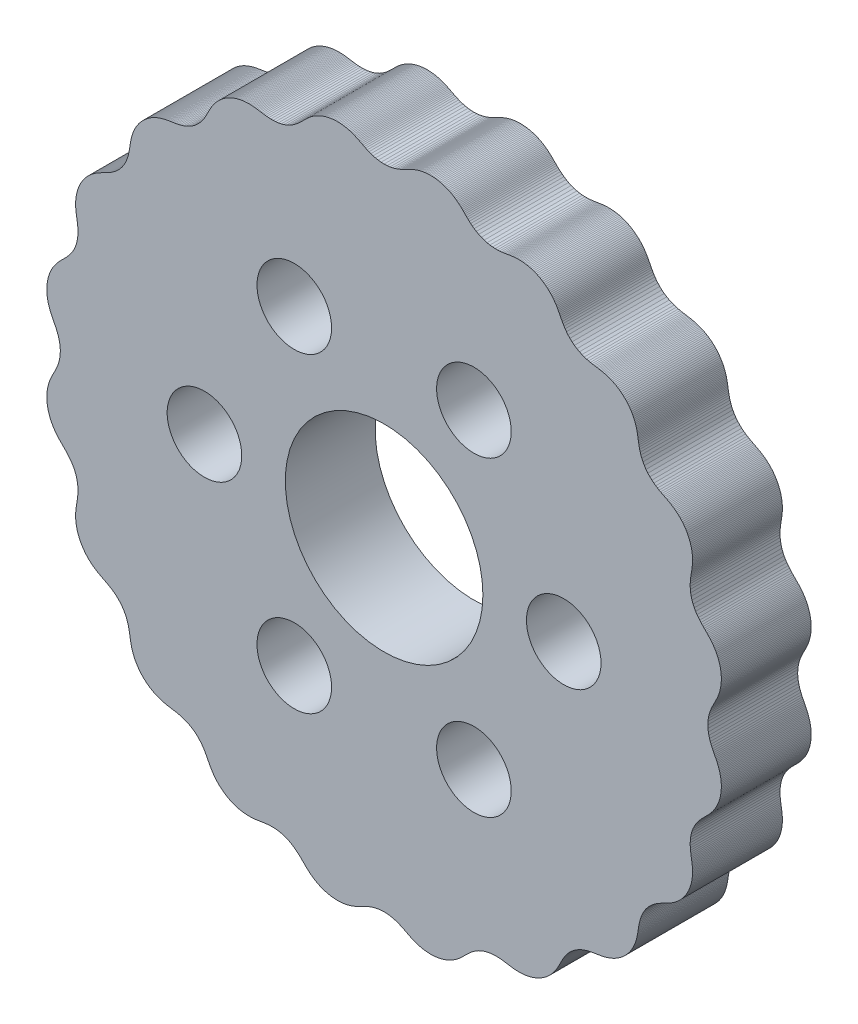
SolidWorks part; units mm, degrees
ref_plane "Front Plane" through (0, 0, 0) normal (0, 0, 1) x (1, 0, 0)
ref_plane "Top Plane" through (0, 0, 0) normal (0, 1, 0) x (1, 0, 0)
ref_plane "Right Plane" through (0, 0, 0) normal (1, 0, 0) x (0, 0, -1)
sketch "Model" plane through (0, 0, 0) normal (0, 0, 1) x (1, 0, 0)
  line L0 (36.0476, 0) -> (36.0614, -0.3338)
  line L1 (36.0614, -0.3338) -> (36.1007, -0.6555)
  line L2 (36.1007, -0.6555) -> (36.1604, -0.9553)
  line L3 (36.1604, -0.9553) -> (36.234, -1.2278)
  line L4 (36.234, -1.2278) -> (36.315, -1.4714)
  line L5 (36.315, -1.4714) -> (36.3985, -1.6875)
  line L6 (36.3985, -1.6875) -> (36.481, -1.8794)
  line L7 (36.481, -1.8794) -> (36.5605, -2.051)
  line L8 (36.5605, -2.051) -> (36.6361, -2.2061)
  line L9 (36.6361, -2.2061) -> (36.7077, -2.3484)
  line L10 (36.7077, -2.3484) -> (36.7755, -2.4811)
  line L11 (36.7755, -2.4811) -> (36.8398, -2.6068)
  line L12 (36.8398, -2.6068) -> (36.901, -2.7278)
  line L13 (36.901, -2.7278) -> (36.9595, -2.8459)
  line L14 (36.9595, -2.8459) -> (37.0156, -2.9627)
  line L15 (37.0156, -2.9627) -> (37.0695, -3.0793)
  line L16 (37.0695, -3.0793) -> (37.1214, -3.1968)
  line L17 (37.1214, -3.1968) -> (37.1711, -3.3159)
  line L18 (37.1711, -3.3159) -> (37.2188, -3.4373)
  line L19 (37.2188, -3.4373) -> (37.2642, -3.5615)
  line L20 (37.2642, -3.5615) -> (37.3071, -3.6888)
  line L21 (37.3071, -3.6888) -> (37.3474, -3.8194)
  line L22 (37.3474, -3.8194) -> (37.3847, -3.9534)
  line L23 (37.3847, -3.9534) -> (37.4188, -4.0909)
  line L24 (37.4188, -4.0909) -> (37.4494, -4.2319)
  line L25 (37.4494, -4.2319) -> (37.4763, -4.3762)
  line L26 (37.4763, -4.3762) -> (37.4991, -4.5236)
  line L27 (37.4991, -4.5236) -> (37.5175, -4.674)
  line L28 (37.5175, -4.674) -> (37.5313, -4.8269)
  line L29 (37.5313, -4.8269) -> (37.5403, -4.982)
  line L30 (37.5403, -4.982) -> (37.5443, -5.139)
  line L31 (37.5443, -5.139) -> (37.5431, -5.2975)
  line L32 (37.5431, -5.2975) -> (37.5367, -5.457)
  line L33 (37.5367, -5.457) -> (37.5249, -5.6171)
  line L34 (37.5249, -5.6171) -> (37.5077, -5.7773)
  line L35 (37.5077, -5.7773) -> (37.4851, -5.9371)
  line L36 (37.4851, -5.9371) -> (37.4572, -6.096)
  line L37 (37.4572, -6.096) -> (37.4241, -6.2537)
  line L38 (37.4241, -6.2537) -> (37.3858, -6.4095)
  line L39 (37.3858, -6.4095) -> (37.3427, -6.5632)
  line L40 (37.3427, -6.5632) -> (37.2948, -6.7143)
  line L41 (37.2948, -6.7143) -> (37.2425, -6.8624)
  line L42 (37.2425, -6.8624) -> (37.186, -7.0072)
  line L43 (37.186, -7.0072) -> (37.1256, -7.1483)
  line L44 (37.1256, -7.1483) -> (37.0616, -7.2856)
  line L45 (37.0616, -7.2856) -> (36.9944, -7.4188)
  line L46 (36.9944, -7.4188) -> (36.9243, -7.5477)
  line L47 (36.9243, -7.5477) -> (36.8516, -7.6723)
  line L48 (36.8516, -7.6723) -> (36.7766, -7.7926)
  line L49 (36.7766, -7.7926) -> (36.6997, -7.9085)
  line L50 (36.6997, -7.9085) -> (36.621, -8.0203)
  line L51 (36.621, -8.0203) -> (36.5409, -8.1281)
  line L52 (36.5409, -8.1281) -> (36.4594, -8.2322)
  line L53 (36.4594, -8.2322) -> (36.3765, -8.3329)
  line L54 (36.3765, -8.3329) -> (36.2924, -8.4308)
  line L55 (36.2924, -8.4308) -> (36.2068, -8.5265)
  line L56 (36.2068, -8.5265) -> (36.1195, -8.6208)
  line L57 (36.1195, -8.6208) -> (36.03, -8.7145)
  line L58 (36.03, -8.7145) -> (35.9379, -8.8087)
  line L59 (35.9379, -8.8087) -> (35.8423, -8.9049)
  line L60 (35.8423, -8.9049) -> (35.7423, -9.0046)
  line L61 (35.7423, -9.0046) -> (35.6368, -9.1098)
  line L62 (35.6368, -9.1098) -> (35.5248, -9.223)
  line L63 (35.5248, -9.223) -> (35.4049, -9.3472)
  line L64 (35.4049, -9.3472) -> (35.2762, -9.4858)
  line L65 (35.2762, -9.4858) -> (35.1385, -9.6428)
  line L66 (35.1385, -9.6428) -> (34.9923, -9.8226)
  line L67 (34.9923, -9.8226) -> (34.84, -10.0292)
  line L68 (34.84, -10.0292) -> (34.6858, -10.2656)
  line L69 (34.6858, -10.2656) -> (34.5364, -10.5323)
  line L70 (34.5364, -10.5323) -> (34.3996, -10.8261)
  line L71 (34.3996, -10.8261) -> (34.2833, -11.1393)
  line L72 (34.2833, -11.1393) -> (34.1932, -11.4611)
  line L73 (34.1932, -11.4611) -> (34.1312, -11.7791)
  line L74 (34.1312, -11.7791) -> (34.0954, -12.0827)
  line L75 (34.0954, -12.0827) -> (34.0812, -12.3646)
  line L76 (34.0812, -12.3646) -> (34.083, -12.6213)
  line L77 (34.083, -12.6213) -> (34.0956, -12.8527)
  line L78 (34.0956, -12.8527) -> (34.1147, -13.0607)
  line L79 (34.1147, -13.0607) -> (34.1373, -13.2484)
  line L80 (34.1373, -13.2484) -> (34.1613, -13.4193)
  line L81 (34.1613, -13.4193) -> (34.1854, -13.5768)
  line L82 (34.1854, -13.5768) -> (34.2089, -13.7239)
  line L83 (34.2089, -13.7239) -> (34.2312, -13.8634)
  line L84 (34.2312, -13.8634) -> (34.252, -13.9973)
  line L85 (34.252, -13.9973) -> (34.2711, -14.1278)
  line L86 (34.2711, -14.1278) -> (34.2884, -14.2561)
  line L87 (34.2884, -14.2561) -> (34.3037, -14.3837)
  line L88 (34.3037, -14.3837) -> (34.3167, -14.5114)
  line L89 (34.3167, -14.5114) -> (34.3272, -14.6401)
  line L90 (34.3272, -14.6401) -> (34.335, -14.7703)
  line L91 (34.335, -14.7703) -> (34.3398, -14.9024)
  line L92 (34.3398, -14.9024) -> (34.3413, -15.0367)
  line L93 (34.3413, -15.0367) -> (34.3392, -15.1734)
  line L94 (34.3392, -15.1734) -> (34.3333, -15.3124)
  line L95 (34.3333, -15.3124) -> (34.3232, -15.4538)
  line L96 (34.3232, -15.4538) -> (34.3088, -15.5973)
  line L97 (34.3088, -15.5973) -> (34.2897, -15.7428)
  line L98 (34.2897, -15.7428) -> (34.2658, -15.8901)
  line L99 (34.2658, -15.8901) -> (34.2369, -16.0387)
  line L100 (34.2369, -16.0387) -> (34.2028, -16.1884)
  line L101 (34.2028, -16.1884) -> (34.1634, -16.3388)
  line L102 (34.1634, -16.3388) -> (34.1187, -16.4893)
  line L103 (34.1187, -16.4893) -> (34.0686, -16.6397)
  line L104 (34.0686, -16.6397) -> (34.0132, -16.7894)
  line L105 (34.0132, -16.7894) -> (33.9525, -16.938)
  line L106 (33.9525, -16.938) -> (33.8867, -17.085)
  line L107 (33.8867, -17.085) -> (33.8158, -17.23)
  line L108 (33.8158, -17.23) -> (33.7402, -17.3726)
  line L109 (33.7402, -17.3726) -> (33.6599, -17.5123)
  line L110 (33.6599, -17.5123) -> (33.5754, -17.6487)
  line L111 (33.5754, -17.6487) -> (33.4868, -17.7815)
  line L112 (33.4868, -17.7815) -> (33.3946, -17.9104)
  line L113 (33.3946, -17.9104) -> (33.2991, -18.0351)
  line L114 (33.2991, -18.0351) -> (33.2006, -18.1553)
  line L115 (33.2006, -18.1553) -> (33.0995, -18.2709)
  line L116 (33.0995, -18.2709) -> (32.9963, -18.3817)
  line L117 (32.9963, -18.3817) -> (32.8912, -18.4876)
  line L118 (32.8912, -18.4876) -> (32.7847, -18.5885)
  line L119 (32.7847, -18.5885) -> (32.6771, -18.6846)
  line L120 (32.6771, -18.6846) -> (32.5686, -18.7758)
  line L121 (32.5686, -18.7758) -> (32.4596, -18.8623)
  line L122 (32.4596, -18.8623) -> (32.3503, -18.9443)
  line L123 (32.3503, -18.9443) -> (32.2407, -19.022)
  line L124 (32.2407, -19.022) -> (32.131, -19.0958)
  line L125 (32.131, -19.0958) -> (32.0211, -19.166)
  line L126 (32.0211, -19.166) -> (31.9108, -19.2332)
  line L127 (31.9108, -19.2332) -> (31.7998, -19.2977)
  line L128 (31.7998, -19.2977) -> (31.6877, -19.3604)
  line L129 (31.6877, -19.3604) -> (31.5737, -19.4219)
  line L130 (31.5737, -19.4219) -> (31.4569, -19.483)
  line L131 (31.4569, -19.483) -> (31.3363, -19.5449)
  line L132 (31.3363, -19.5449) -> (31.2104, -19.6088)
  line L133 (31.2104, -19.6088) -> (31.0776, -19.6763)
  line L134 (31.0776, -19.6763) -> (30.936, -19.7494)
  line L135 (30.936, -19.7494) -> (30.7836, -19.8304)
  line L136 (30.7836, -19.8304) -> (30.6184, -19.9225)
  line L137 (30.6184, -19.9225) -> (30.4389, -20.0293)
  line L138 (30.4389, -20.0293) -> (30.2443, -20.1551)
  line L139 (30.2443, -20.1551) -> (30.0356, -20.3045)
  line L140 (30.0356, -20.3045) -> (29.8159, -20.4817)
  line L141 (29.8159, -20.4817) -> (29.5914, -20.6892)
  line L142 (29.5914, -20.6892) -> (29.3705, -20.9263)
  line L143 (29.3705, -20.9263) -> (29.1631, -21.1883)
  line L144 (29.1631, -21.1883) -> (28.978, -21.4664)
  line L145 (28.978, -21.4664) -> (28.8208, -21.7497)
  line L146 (28.8208, -21.7497) -> (28.6929, -22.0274)
  line L147 (28.6929, -22.0274) -> (28.5922, -22.2911)
  line L148 (28.5922, -22.2911) -> (28.5146, -22.5358)
  line L149 (28.5146, -22.5358) -> (28.4551, -22.7598)
  line L150 (28.4551, -22.7598) -> (28.409, -22.9635)
  line L151 (28.409, -22.9635) -> (28.3725, -23.149)
  line L152 (28.3725, -23.149) -> (28.3425, -23.319)
  line L153 (28.3425, -23.319) -> (28.3168, -23.4762)
  line L154 (28.3168, -23.4762) -> (28.2936, -23.6234)
  line L155 (28.2936, -23.6234) -> (28.2718, -23.7629)
  line L156 (28.2718, -23.7629) -> (28.2502, -23.8967)
  line L157 (28.2502, -23.8967) -> (28.2281, -24.0267)
  line L158 (28.2281, -24.0267) -> (28.2049, -24.1541)
  line L159 (28.2049, -24.1541) -> (28.1799, -24.2801)
  line L160 (28.1799, -24.2801) -> (28.1528, -24.4056)
  line L161 (28.1528, -24.4056) -> (28.1231, -24.5313)
  line L162 (28.1231, -24.5313) -> (28.0902, -24.6575)
  line L163 (28.0902, -24.6575) -> (28.0539, -24.7846)
  line L164 (28.0539, -24.7846) -> (28.0139, -24.9128)
  line L165 (28.0139, -24.9128) -> (27.9697, -25.0421)
  line L166 (27.9697, -25.0421) -> (27.9211, -25.1725)
  line L167 (27.9211, -25.1725) -> (27.8679, -25.3039)
  line L168 (27.8679, -25.3039) -> (27.8098, -25.4359)
  line L169 (27.8098, -25.4359) -> (27.7467, -25.5684)
  line L170 (27.7467, -25.5684) -> (27.6784, -25.7011)
  line L171 (27.6784, -25.7011) -> (27.605, -25.8335)
  line L172 (27.605, -25.8335) -> (27.5263, -25.9653)
  line L173 (27.5263, -25.9653) -> (27.4424, -26.0962)
  line L174 (27.4424, -26.0962) -> (27.3533, -26.2256)
  line L175 (27.3533, -26.2256) -> (27.2592, -26.3531)
  line L176 (27.2592, -26.3531) -> (27.1603, -26.4783)
  line L177 (27.1603, -26.4783) -> (27.0566, -26.6009)
  line L178 (27.0566, -26.6009) -> (26.9486, -26.7204)
  line L179 (26.9486, -26.7204) -> (26.8364, -26.8364)
  line L180 (26.8364, -26.8364) -> (26.7204, -26.9486)
  line L181 (26.7204, -26.9486) -> (26.6009, -27.0566)
  line L182 (26.6009, -27.0566) -> (26.4783, -27.1603)
  line L183 (26.4783, -27.1603) -> (26.3531, -27.2592)
  line L184 (26.3531, -27.2592) -> (26.2256, -27.3533)
  line L185 (26.2256, -27.3533) -> (26.0962, -27.4424)
  line L186 (26.0962, -27.4424) -> (25.9653, -27.5263)
  line L187 (25.9653, -27.5263) -> (25.8335, -27.605)
  line L188 (25.8335, -27.605) -> (25.7011, -27.6784)
  line L189 (25.7011, -27.6784) -> (25.5684, -27.7467)
  line L190 (25.5684, -27.7467) -> (25.4359, -27.8098)
  line L191 (25.4359, -27.8098) -> (25.3039, -27.8679)
  line L192 (25.3039, -27.8679) -> (25.1725, -27.9211)
  line L193 (25.1725, -27.9211) -> (25.0421, -27.9697)
  line L194 (25.0421, -27.9697) -> (24.9128, -28.0139)
  line L195 (24.9128, -28.0139) -> (24.7846, -28.0539)
  line L196 (24.7846, -28.0539) -> (24.6575, -28.0902)
  line L197 (24.6575, -28.0902) -> (24.5313, -28.1231)
  line L198 (24.5313, -28.1231) -> (24.4056, -28.1528)
  line L199 (24.4056, -28.1528) -> (24.2801, -28.1799)
  line L200 (24.2801, -28.1799) -> (24.1541, -28.2049)
  line L201 (24.1541, -28.2049) -> (24.0267, -28.2281)
  line L202 (24.0267, -28.2281) -> (23.8967, -28.2502)
  line L203 (23.8967, -28.2502) -> (23.7629, -28.2718)
  line L204 (23.7629, -28.2718) -> (23.6234, -28.2936)
  line L205 (23.6234, -28.2936) -> (23.4762, -28.3168)
  line L206 (23.4762, -28.3168) -> (23.319, -28.3425)
  line L207 (23.319, -28.3425) -> (23.149, -28.3725)
  line L208 (23.149, -28.3725) -> (22.9635, -28.409)
  line L209 (22.9635, -28.409) -> (22.7598, -28.4551)
  line L210 (22.7598, -28.4551) -> (22.5358, -28.5146)
  line L211 (22.5358, -28.5146) -> (22.2911, -28.5922)
  line L212 (22.2911, -28.5922) -> (22.0274, -28.6929)
  line L213 (22.0274, -28.6929) -> (21.7497, -28.8208)
  line L214 (21.7497, -28.8208) -> (21.4664, -28.978)
  line L215 (21.4664, -28.978) -> (21.1883, -29.1631)
  line L216 (21.1883, -29.1631) -> (20.9263, -29.3705)
  line L217 (20.9263, -29.3705) -> (20.6892, -29.5914)
  line L218 (20.6892, -29.5914) -> (20.4817, -29.8159)
  line L219 (20.4817, -29.8159) -> (20.3045, -30.0356)
  line L220 (20.3045, -30.0356) -> (20.1551, -30.2443)
  line L221 (20.1551, -30.2443) -> (20.0293, -30.4389)
  line L222 (20.0293, -30.4389) -> (19.9225, -30.6184)
  line L223 (19.9225, -30.6184) -> (19.8304, -30.7836)
  line L224 (19.8304, -30.7836) -> (19.7494, -30.936)
  line L225 (19.7494, -30.936) -> (19.6763, -31.0776)
  line L226 (19.6763, -31.0776) -> (19.6088, -31.2104)
  line L227 (19.6088, -31.2104) -> (19.5449, -31.3363)
  line L228 (19.5449, -31.3363) -> (19.483, -31.4569)
  line L229 (19.483, -31.4569) -> (19.4219, -31.5737)
  line L230 (19.4219, -31.5737) -> (19.3604, -31.6877)
  line L231 (19.3604, -31.6877) -> (19.2977, -31.7998)
  line L232 (19.2977, -31.7998) -> (19.2332, -31.9108)
  line L233 (19.2332, -31.9108) -> (19.166, -32.0211)
  line L234 (19.166, -32.0211) -> (19.0958, -32.131)
  line L235 (19.0958, -32.131) -> (19.022, -32.2407)
  line L236 (19.022, -32.2407) -> (18.9443, -32.3503)
  line L237 (18.9443, -32.3503) -> (18.8623, -32.4596)
  line L238 (18.8623, -32.4596) -> (18.7758, -32.5686)
  line L239 (18.7758, -32.5686) -> (18.6846, -32.6771)
  line L240 (18.6846, -32.6771) -> (18.5885, -32.7847)
  line L241 (18.5885, -32.7847) -> (18.4876, -32.8912)
  line L242 (18.4876, -32.8912) -> (18.3817, -32.9963)
  line L243 (18.3817, -32.9963) -> (18.2709, -33.0995)
  line L244 (18.2709, -33.0995) -> (18.1553, -33.2006)
  line L245 (18.1553, -33.2006) -> (18.0351, -33.2991)
  line L246 (18.0351, -33.2991) -> (17.9104, -33.3946)
  line L247 (17.9104, -33.3946) -> (17.7815, -33.4868)
  line L248 (17.7815, -33.4868) -> (17.6487, -33.5754)
  line L249 (17.6487, -33.5754) -> (17.5123, -33.6599)
  line L250 (17.5123, -33.6599) -> (17.3726, -33.7402)
  line L251 (17.3726, -33.7402) -> (17.23, -33.8158)
  line L252 (17.23, -33.8158) -> (17.085, -33.8867)
  line L253 (17.085, -33.8867) -> (16.938, -33.9525)
  line L254 (16.938, -33.9525) -> (16.7894, -34.0132)
  line L255 (16.7894, -34.0132) -> (16.6397, -34.0686)
  line L256 (16.6397, -34.0686) -> (16.4893, -34.1187)
  line L257 (16.4893, -34.1187) -> (16.3388, -34.1634)
  line L258 (16.3388, -34.1634) -> (16.1884, -34.2028)
  line L259 (16.1884, -34.2028) -> (16.0387, -34.2369)
  line L260 (16.0387, -34.2369) -> (15.8901, -34.2658)
  line L261 (15.8901, -34.2658) -> (15.7428, -34.2897)
  line L262 (15.7428, -34.2897) -> (15.5973, -34.3088)
  line L263 (15.5973, -34.3088) -> (15.4538, -34.3232)
  line L264 (15.4538, -34.3232) -> (15.3124, -34.3333)
  line L265 (15.3124, -34.3333) -> (15.1734, -34.3392)
  line L266 (15.1734, -34.3392) -> (15.0367, -34.3413)
  line L267 (15.0367, -34.3413) -> (14.9024, -34.3398)
  line L268 (14.9024, -34.3398) -> (14.7703, -34.335)
  line L269 (14.7703, -34.335) -> (14.6401, -34.3272)
  line L270 (14.6401, -34.3272) -> (14.5114, -34.3167)
  line L271 (14.5114, -34.3167) -> (14.3837, -34.3037)
  line L272 (14.3837, -34.3037) -> (14.2561, -34.2884)
  line L273 (14.2561, -34.2884) -> (14.1278, -34.2711)
  line L274 (14.1278, -34.2711) -> (13.9973, -34.252)
  line L275 (13.9973, -34.252) -> (13.8634, -34.2312)
  line L276 (13.8634, -34.2312) -> (13.7239, -34.2089)
  line L277 (13.7239, -34.2089) -> (13.5768, -34.1854)
  line L278 (13.5768, -34.1854) -> (13.4193, -34.1613)
  line L279 (13.4193, -34.1613) -> (13.2484, -34.1373)
  line L280 (13.2484, -34.1373) -> (13.0607, -34.1147)
  line L281 (13.0607, -34.1147) -> (12.8527, -34.0956)
  line L282 (12.8527, -34.0956) -> (12.6213, -34.083)
  line L283 (12.6213, -34.083) -> (12.3646, -34.0812)
  line L284 (12.3646, -34.0812) -> (12.0827, -34.0954)
  line L285 (12.0827, -34.0954) -> (11.7791, -34.1312)
  line L286 (11.7791, -34.1312) -> (11.4611, -34.1932)
  line L287 (11.4611, -34.1932) -> (11.1393, -34.2833)
  line L288 (11.1393, -34.2833) -> (10.8261, -34.3996)
  line L289 (10.8261, -34.3996) -> (10.5323, -34.5364)
  line L290 (10.5323, -34.5364) -> (10.2656, -34.6858)
  line L291 (10.2656, -34.6858) -> (10.0292, -34.84)
  line L292 (10.0292, -34.84) -> (9.8226, -34.9923)
  line L293 (9.8226, -34.9923) -> (9.6428, -35.1385)
  line L294 (9.6428, -35.1385) -> (9.4858, -35.2762)
  line L295 (9.4858, -35.2762) -> (9.3472, -35.4049)
  line L296 (9.3472, -35.4049) -> (9.223, -35.5248)
  line L297 (9.223, -35.5248) -> (9.1098, -35.6368)
  line L298 (9.1098, -35.6368) -> (9.0046, -35.7423)
  line L299 (9.0046, -35.7423) -> (8.9049, -35.8423)
  line L300 (8.9049, -35.8423) -> (8.8087, -35.9379)
  line L301 (8.8087, -35.9379) -> (8.7145, -36.03)
  line L302 (8.7145, -36.03) -> (8.6208, -36.1195)
  line L303 (8.6208, -36.1195) -> (8.5265, -36.2068)
  line L304 (8.5265, -36.2068) -> (8.4308, -36.2924)
  line L305 (8.4308, -36.2924) -> (8.3329, -36.3765)
  line L306 (8.3329, -36.3765) -> (8.2322, -36.4594)
  line L307 (8.2322, -36.4594) -> (8.1281, -36.5409)
  line L308 (8.1281, -36.5409) -> (8.0203, -36.621)
  line L309 (8.0203, -36.621) -> (7.9085, -36.6997)
  line L310 (7.9085, -36.6997) -> (7.7926, -36.7766)
  line L311 (7.7926, -36.7766) -> (7.6723, -36.8516)
  line L312 (7.6723, -36.8516) -> (7.5477, -36.9243)
  line L313 (7.5477, -36.9243) -> (7.4188, -36.9944)
  line L314 (7.4188, -36.9944) -> (7.2856, -37.0616)
  line L315 (7.2856, -37.0616) -> (7.1483, -37.1256)
  line L316 (7.1483, -37.1256) -> (7.0072, -37.186)
  line L317 (7.0072, -37.186) -> (6.8624, -37.2425)
  line L318 (6.8624, -37.2425) -> (6.7143, -37.2948)
  line L319 (6.7143, -37.2948) -> (6.5632, -37.3427)
  line L320 (6.5632, -37.3427) -> (6.4095, -37.3858)
  line L321 (6.4095, -37.3858) -> (6.2537, -37.4241)
  line L322 (6.2537, -37.4241) -> (6.096, -37.4572)
  line L323 (6.096, -37.4572) -> (5.9371, -37.4851)
  line L324 (5.9371, -37.4851) -> (5.7773, -37.5077)
  line L325 (5.7773, -37.5077) -> (5.6171, -37.5249)
  line L326 (5.6171, -37.5249) -> (5.457, -37.5367)
  line L327 (5.457, -37.5367) -> (5.2975, -37.5431)
  line L328 (5.2975, -37.5431) -> (5.139, -37.5443)
  line L329 (5.139, -37.5443) -> (4.982, -37.5403)
  line L330 (4.982, -37.5403) -> (4.8269, -37.5313)
  line L331 (4.8269, -37.5313) -> (4.674, -37.5175)
  line L332 (4.674, -37.5175) -> (4.5236, -37.4991)
  line L333 (4.5236, -37.4991) -> (4.3762, -37.4763)
  line L334 (4.3762, -37.4763) -> (4.2319, -37.4494)
  line L335 (4.2319, -37.4494) -> (4.0909, -37.4188)
  line L336 (4.0909, -37.4188) -> (3.9534, -37.3847)
  line L337 (3.9534, -37.3847) -> (3.8194, -37.3474)
  line L338 (3.8194, -37.3474) -> (3.6888, -37.3071)
  line L339 (3.6888, -37.3071) -> (3.5615, -37.2642)
  line L340 (3.5615, -37.2642) -> (3.4373, -37.2188)
  line L341 (3.4373, -37.2188) -> (3.3159, -37.1711)
  line L342 (3.3159, -37.1711) -> (3.1968, -37.1214)
  line L343 (3.1968, -37.1214) -> (3.0793, -37.0695)
  line L344 (3.0793, -37.0695) -> (2.9627, -37.0156)
  line L345 (2.9627, -37.0156) -> (2.8459, -36.9595)
  line L346 (2.8459, -36.9595) -> (2.7278, -36.901)
  line L347 (2.7278, -36.901) -> (2.6068, -36.8398)
  line L348 (2.6068, -36.8398) -> (2.4811, -36.7755)
  line L349 (2.4811, -36.7755) -> (2.3484, -36.7077)
  line L350 (2.3484, -36.7077) -> (2.2061, -36.6361)
  line L351 (2.2061, -36.6361) -> (2.051, -36.5605)
  line L352 (2.051, -36.5605) -> (1.8794, -36.481)
  line L353 (1.8794, -36.481) -> (1.6875, -36.3985)
  line L354 (1.6875, -36.3985) -> (1.4714, -36.315)
  line L355 (1.4714, -36.315) -> (1.2278, -36.234)
  line L356 (1.2278, -36.234) -> (0.9553, -36.1604)
  line L357 (0.9553, -36.1604) -> (0.6555, -36.1007)
  line L358 (0.6555, -36.1007) -> (0.3338, -36.0614)
  line L359 (0.3338, -36.0614) -> (0, -36.0476)
  line L360 (0, -36.0476) -> (-0.3338, -36.0614)
  line L361 (-0.3338, -36.0614) -> (-0.6555, -36.1007)
  line L362 (-0.6555, -36.1007) -> (-0.9553, -36.1604)
  line L363 (-0.9553, -36.1604) -> (-1.2278, -36.234)
  line L364 (-1.2278, -36.234) -> (-1.4714, -36.315)
  line L365 (-1.4714, -36.315) -> (-1.6875, -36.3985)
  line L366 (-1.6875, -36.3985) -> (-1.8794, -36.481)
  line L367 (-1.8794, -36.481) -> (-2.051, -36.5605)
  line L368 (-2.051, -36.5605) -> (-2.2061, -36.6361)
  line L369 (-2.2061, -36.6361) -> (-2.3484, -36.7077)
  line L370 (-2.3484, -36.7077) -> (-2.4811, -36.7755)
  line L371 (-2.4811, -36.7755) -> (-2.6068, -36.8398)
  line L372 (-2.6068, -36.8398) -> (-2.7278, -36.901)
  line L373 (-2.7278, -36.901) -> (-2.8459, -36.9595)
  line L374 (-2.8459, -36.9595) -> (-2.9627, -37.0156)
  line L375 (-2.9627, -37.0156) -> (-3.0793, -37.0695)
  line L376 (-3.0793, -37.0695) -> (-3.1968, -37.1214)
  line L377 (-3.1968, -37.1214) -> (-3.3159, -37.1711)
  line L378 (-3.3159, -37.1711) -> (-3.4373, -37.2188)
  line L379 (-3.4373, -37.2188) -> (-3.5615, -37.2642)
  line L380 (-3.5615, -37.2642) -> (-3.6888, -37.3071)
  line L381 (-3.6888, -37.3071) -> (-3.8194, -37.3474)
  line L382 (-3.8194, -37.3474) -> (-3.9534, -37.3847)
  line L383 (-3.9534, -37.3847) -> (-4.0909, -37.4188)
  line L384 (-4.0909, -37.4188) -> (-4.2319, -37.4494)
  line L385 (-4.2319, -37.4494) -> (-4.3762, -37.4763)
  line L386 (-4.3762, -37.4763) -> (-4.5236, -37.4991)
  line L387 (-4.5236, -37.4991) -> (-4.674, -37.5175)
  line L388 (-4.674, -37.5175) -> (-4.8269, -37.5313)
  line L389 (-4.8269, -37.5313) -> (-4.982, -37.5403)
  line L390 (-4.982, -37.5403) -> (-5.139, -37.5443)
  line L391 (-5.139, -37.5443) -> (-5.2975, -37.5431)
  line L392 (-5.2975, -37.5431) -> (-5.457, -37.5367)
  line L393 (-5.457, -37.5367) -> (-5.6171, -37.5249)
  line L394 (-5.6171, -37.5249) -> (-5.7773, -37.5077)
  line L395 (-5.7773, -37.5077) -> (-5.9371, -37.4851)
  line L396 (-5.9371, -37.4851) -> (-6.096, -37.4572)
  line L397 (-6.096, -37.4572) -> (-6.2537, -37.4241)
  line L398 (-6.2537, -37.4241) -> (-6.4095, -37.3858)
  line L399 (-6.4095, -37.3858) -> (-6.5632, -37.3427)
  line L400 (-6.5632, -37.3427) -> (-6.7143, -37.2948)
  line L401 (-6.7143, -37.2948) -> (-6.8624, -37.2425)
  line L402 (-6.8624, -37.2425) -> (-7.0072, -37.186)
  line L403 (-7.0072, -37.186) -> (-7.1483, -37.1256)
  line L404 (-7.1483, -37.1256) -> (-7.2856, -37.0616)
  line L405 (-7.2856, -37.0616) -> (-7.4188, -36.9944)
  line L406 (-7.4188, -36.9944) -> (-7.5477, -36.9243)
  line L407 (-7.5477, -36.9243) -> (-7.6723, -36.8516)
  line L408 (-7.6723, -36.8516) -> (-7.7926, -36.7766)
  line L409 (-7.7926, -36.7766) -> (-7.9085, -36.6997)
  line L410 (-7.9085, -36.6997) -> (-8.0203, -36.621)
  line L411 (-8.0203, -36.621) -> (-8.1281, -36.5409)
  line L412 (-8.1281, -36.5409) -> (-8.2322, -36.4594)
  line L413 (-8.2322, -36.4594) -> (-8.3329, -36.3765)
  line L414 (-8.3329, -36.3765) -> (-8.4308, -36.2924)
  line L415 (-8.4308, -36.2924) -> (-8.5265, -36.2068)
  line L416 (-8.5265, -36.2068) -> (-8.6208, -36.1195)
  line L417 (-8.6208, -36.1195) -> (-8.7145, -36.03)
  line L418 (-8.7145, -36.03) -> (-8.8087, -35.9379)
  line L419 (-8.8087, -35.9379) -> (-8.9049, -35.8423)
  line L420 (-8.9049, -35.8423) -> (-9.0046, -35.7423)
  line L421 (-9.0046, -35.7423) -> (-9.1098, -35.6368)
  line L422 (-9.1098, -35.6368) -> (-9.223, -35.5248)
  line L423 (-9.223, -35.5248) -> (-9.3472, -35.4049)
  line L424 (-9.3472, -35.4049) -> (-9.4858, -35.2762)
  line L425 (-9.4858, -35.2762) -> (-9.6428, -35.1385)
  line L426 (-9.6428, -35.1385) -> (-9.8226, -34.9923)
  line L427 (-9.8226, -34.9923) -> (-10.0292, -34.84)
  line L428 (-10.0292, -34.84) -> (-10.2656, -34.6858)
  line L429 (-10.2656, -34.6858) -> (-10.5323, -34.5364)
  line L430 (-10.5323, -34.5364) -> (-10.8261, -34.3996)
  line L431 (-10.8261, -34.3996) -> (-11.1393, -34.2833)
  line L432 (-11.1393, -34.2833) -> (-11.4611, -34.1932)
  line L433 (-11.4611, -34.1932) -> (-11.7791, -34.1312)
  line L434 (-11.7791, -34.1312) -> (-12.0827, -34.0954)
  line L435 (-12.0827, -34.0954) -> (-12.3646, -34.0812)
  line L436 (-12.3646, -34.0812) -> (-12.6213, -34.083)
  line L437 (-12.6213, -34.083) -> (-12.8527, -34.0956)
  line L438 (-12.8527, -34.0956) -> (-13.0607, -34.1147)
  line L439 (-13.0607, -34.1147) -> (-13.2484, -34.1373)
  line L440 (-13.2484, -34.1373) -> (-13.4193, -34.1613)
  line L441 (-13.4193, -34.1613) -> (-13.5768, -34.1854)
  line L442 (-13.5768, -34.1854) -> (-13.7239, -34.2089)
  line L443 (-13.7239, -34.2089) -> (-13.8634, -34.2312)
  line L444 (-13.8634, -34.2312) -> (-13.9973, -34.252)
  line L445 (-13.9973, -34.252) -> (-14.1278, -34.2711)
  line L446 (-14.1278, -34.2711) -> (-14.2561, -34.2884)
  line L447 (-14.2561, -34.2884) -> (-14.3837, -34.3037)
  line L448 (-14.3837, -34.3037) -> (-14.5114, -34.3167)
  line L449 (-14.5114, -34.3167) -> (-14.6401, -34.3272)
  line L450 (-14.6401, -34.3272) -> (-14.7703, -34.335)
  line L451 (-14.7703, -34.335) -> (-14.9024, -34.3398)
  line L452 (-14.9024, -34.3398) -> (-15.0367, -34.3413)
  line L453 (-15.0367, -34.3413) -> (-15.1734, -34.3392)
  line L454 (-15.1734, -34.3392) -> (-15.3124, -34.3333)
  line L455 (-15.3124, -34.3333) -> (-15.4538, -34.3232)
  line L456 (-15.4538, -34.3232) -> (-15.5973, -34.3088)
  line L457 (-15.5973, -34.3088) -> (-15.7428, -34.2897)
  line L458 (-15.7428, -34.2897) -> (-15.8901, -34.2658)
  line L459 (-15.8901, -34.2658) -> (-16.0387, -34.2369)
  line L460 (-16.0387, -34.2369) -> (-16.1884, -34.2028)
  line L461 (-16.1884, -34.2028) -> (-16.3388, -34.1634)
  line L462 (-16.3388, -34.1634) -> (-16.4893, -34.1187)
  line L463 (-16.4893, -34.1187) -> (-16.6397, -34.0686)
  line L464 (-16.6397, -34.0686) -> (-16.7894, -34.0132)
  line L465 (-16.7894, -34.0132) -> (-16.938, -33.9525)
  line L466 (-16.938, -33.9525) -> (-17.085, -33.8867)
  line L467 (-17.085, -33.8867) -> (-17.23, -33.8158)
  line L468 (-17.23, -33.8158) -> (-17.3726, -33.7402)
  line L469 (-17.3726, -33.7402) -> (-17.5123, -33.6599)
  line L470 (-17.5123, -33.6599) -> (-17.6487, -33.5754)
  line L471 (-17.6487, -33.5754) -> (-17.7815, -33.4868)
  line L472 (-17.7815, -33.4868) -> (-17.9104, -33.3946)
  line L473 (-17.9104, -33.3946) -> (-18.0351, -33.2991)
  line L474 (-18.0351, -33.2991) -> (-18.1553, -33.2006)
  line L475 (-18.1553, -33.2006) -> (-18.2709, -33.0995)
  line L476 (-18.2709, -33.0995) -> (-18.3817, -32.9963)
  line L477 (-18.3817, -32.9963) -> (-18.4876, -32.8912)
  line L478 (-18.4876, -32.8912) -> (-18.5885, -32.7847)
  line L479 (-18.5885, -32.7847) -> (-18.6846, -32.6771)
  line L480 (-18.6846, -32.6771) -> (-18.7758, -32.5686)
  line L481 (-18.7758, -32.5686) -> (-18.8623, -32.4596)
  line L482 (-18.8623, -32.4596) -> (-18.9443, -32.3503)
  line L483 (-18.9443, -32.3503) -> (-19.022, -32.2407)
  line L484 (-19.022, -32.2407) -> (-19.0958, -32.131)
  line L485 (-19.0958, -32.131) -> (-19.166, -32.0211)
  line L486 (-19.166, -32.0211) -> (-19.2332, -31.9108)
  line L487 (-19.2332, -31.9108) -> (-19.2977, -31.7998)
  line L488 (-19.2977, -31.7998) -> (-19.3604, -31.6877)
  line L489 (-19.3604, -31.6877) -> (-19.4219, -31.5737)
  line L490 (-19.4219, -31.5737) -> (-19.483, -31.4569)
  line L491 (-19.483, -31.4569) -> (-19.5449, -31.3363)
  line L492 (-19.5449, -31.3363) -> (-19.6088, -31.2104)
  line L493 (-19.6088, -31.2104) -> (-19.6763, -31.0776)
  line L494 (-19.6763, -31.0776) -> (-19.7494, -30.936)
  line L495 (-19.7494, -30.936) -> (-19.8304, -30.7836)
  line L496 (-19.8304, -30.7836) -> (-19.9225, -30.6184)
  line L497 (-19.9225, -30.6184) -> (-20.0293, -30.4389)
  line L498 (-20.0293, -30.4389) -> (-20.1551, -30.2443)
  line L499 (-20.1551, -30.2443) -> (-20.3045, -30.0356)
  line L500 (-20.3045, -30.0356) -> (-20.4817, -29.8159)
  line L501 (-20.4817, -29.8159) -> (-20.6892, -29.5914)
  line L502 (-20.6892, -29.5914) -> (-20.9263, -29.3705)
  line L503 (-20.9263, -29.3705) -> (-21.1883, -29.1631)
  line L504 (-21.1883, -29.1631) -> (-21.4664, -28.978)
  line L505 (-21.4664, -28.978) -> (-21.7497, -28.8208)
  line L506 (-21.7497, -28.8208) -> (-22.0274, -28.6929)
  line L507 (-22.0274, -28.6929) -> (-22.2911, -28.5922)
  line L508 (-22.2911, -28.5922) -> (-22.5358, -28.5146)
  line L509 (-22.5358, -28.5146) -> (-22.7598, -28.4551)
  line L510 (-22.7598, -28.4551) -> (-22.9635, -28.409)
  line L511 (-22.9635, -28.409) -> (-23.149, -28.3725)
  line L512 (-23.149, -28.3725) -> (-23.319, -28.3425)
  line L513 (-23.319, -28.3425) -> (-23.4762, -28.3168)
  line L514 (-23.4762, -28.3168) -> (-23.6234, -28.2936)
  line L515 (-23.6234, -28.2936) -> (-23.7629, -28.2718)
  line L516 (-23.7629, -28.2718) -> (-23.8967, -28.2502)
  line L517 (-23.8967, -28.2502) -> (-24.0267, -28.2281)
  line L518 (-24.0267, -28.2281) -> (-24.1541, -28.2049)
  line L519 (-24.1541, -28.2049) -> (-24.2801, -28.1799)
  line L520 (-24.2801, -28.1799) -> (-24.4056, -28.1528)
  line L521 (-24.4056, -28.1528) -> (-24.5313, -28.1231)
  line L522 (-24.5313, -28.1231) -> (-24.6575, -28.0902)
  line L523 (-24.6575, -28.0902) -> (-24.7846, -28.0539)
  line L524 (-24.7846, -28.0539) -> (-24.9128, -28.0139)
  line L525 (-24.9128, -28.0139) -> (-25.0421, -27.9697)
  line L526 (-25.0421, -27.9697) -> (-25.1725, -27.9211)
  line L527 (-25.1725, -27.9211) -> (-25.3039, -27.8679)
  line L528 (-25.3039, -27.8679) -> (-25.4359, -27.8098)
  line L529 (-25.4359, -27.8098) -> (-25.5684, -27.7467)
  line L530 (-25.5684, -27.7467) -> (-25.7011, -27.6784)
  line L531 (-25.7011, -27.6784) -> (-25.8335, -27.605)
  line L532 (-25.8335, -27.605) -> (-25.9653, -27.5263)
  line L533 (-25.9653, -27.5263) -> (-26.0962, -27.4424)
  line L534 (-26.0962, -27.4424) -> (-26.2256, -27.3533)
  line L535 (-26.2256, -27.3533) -> (-26.3531, -27.2592)
  line L536 (-26.3531, -27.2592) -> (-26.4783, -27.1603)
  line L537 (-26.4783, -27.1603) -> (-26.6009, -27.0566)
  line L538 (-26.6009, -27.0566) -> (-26.7204, -26.9486)
  line L539 (-26.7204, -26.9486) -> (-26.8364, -26.8364)
  line L540 (-26.8364, -26.8364) -> (-26.9486, -26.7204)
  line L541 (-26.9486, -26.7204) -> (-27.0566, -26.6009)
  line L542 (-27.0566, -26.6009) -> (-27.1603, -26.4783)
  line L543 (-27.1603, -26.4783) -> (-27.2592, -26.3531)
  line L544 (-27.2592, -26.3531) -> (-27.3533, -26.2256)
  line L545 (-27.3533, -26.2256) -> (-27.4424, -26.0962)
  line L546 (-27.4424, -26.0962) -> (-27.5263, -25.9653)
  line L547 (-27.5263, -25.9653) -> (-27.605, -25.8335)
  line L548 (-27.605, -25.8335) -> (-27.6784, -25.7011)
  line L549 (-27.6784, -25.7011) -> (-27.7467, -25.5684)
  line L550 (-27.7467, -25.5684) -> (-27.8098, -25.4359)
  line L551 (-27.8098, -25.4359) -> (-27.8679, -25.3039)
  line L552 (-27.8679, -25.3039) -> (-27.9211, -25.1725)
  line L553 (-27.9211, -25.1725) -> (-27.9697, -25.0421)
  line L554 (-27.9697, -25.0421) -> (-28.0139, -24.9128)
  line L555 (-28.0139, -24.9128) -> (-28.0539, -24.7846)
  line L556 (-28.0539, -24.7846) -> (-28.0902, -24.6575)
  line L557 (-28.0902, -24.6575) -> (-28.1231, -24.5313)
  line L558 (-28.1231, -24.5313) -> (-28.1528, -24.4056)
  line L559 (-28.1528, -24.4056) -> (-28.1799, -24.2801)
  line L560 (-28.1799, -24.2801) -> (-28.2049, -24.1541)
  line L561 (-28.2049, -24.1541) -> (-28.2281, -24.0267)
  line L562 (-28.2281, -24.0267) -> (-28.2502, -23.8967)
  line L563 (-28.2502, -23.8967) -> (-28.2718, -23.7629)
  line L564 (-28.2718, -23.7629) -> (-28.2936, -23.6234)
  line L565 (-28.2936, -23.6234) -> (-28.3168, -23.4762)
  line L566 (-28.3168, -23.4762) -> (-28.3425, -23.319)
  line L567 (-28.3425, -23.319) -> (-28.3725, -23.149)
  line L568 (-28.3725, -23.149) -> (-28.409, -22.9635)
  line L569 (-28.409, -22.9635) -> (-28.4551, -22.7598)
  line L570 (-28.4551, -22.7598) -> (-28.5146, -22.5358)
  line L571 (-28.5146, -22.5358) -> (-28.5922, -22.2911)
  line L572 (-28.5922, -22.2911) -> (-28.6929, -22.0274)
  line L573 (-28.6929, -22.0274) -> (-28.8208, -21.7497)
  line L574 (-28.8208, -21.7497) -> (-28.978, -21.4664)
  line L575 (-28.978, -21.4664) -> (-29.1631, -21.1883)
  line L576 (-29.1631, -21.1883) -> (-29.3705, -20.9263)
  line L577 (-29.3705, -20.9263) -> (-29.5914, -20.6892)
  line L578 (-29.5914, -20.6892) -> (-29.8159, -20.4817)
  line L579 (-29.8159, -20.4817) -> (-30.0356, -20.3045)
  line L580 (-30.0356, -20.3045) -> (-30.2443, -20.1551)
  line L581 (-30.2443, -20.1551) -> (-30.4389, -20.0293)
  line L582 (-30.4389, -20.0293) -> (-30.6184, -19.9225)
  line L583 (-30.6184, -19.9225) -> (-30.7836, -19.8304)
  line L584 (-30.7836, -19.8304) -> (-30.936, -19.7494)
  line L585 (-30.936, -19.7494) -> (-31.0776, -19.6763)
  line L586 (-31.0776, -19.6763) -> (-31.2104, -19.6088)
  line L587 (-31.2104, -19.6088) -> (-31.3363, -19.5449)
  line L588 (-31.3363, -19.5449) -> (-31.4569, -19.483)
  line L589 (-31.4569, -19.483) -> (-31.5737, -19.4219)
  line L590 (-31.5737, -19.4219) -> (-31.6877, -19.3604)
  line L591 (-31.6877, -19.3604) -> (-31.7998, -19.2977)
  line L592 (-31.7998, -19.2977) -> (-31.9108, -19.2332)
  line L593 (-31.9108, -19.2332) -> (-32.0211, -19.166)
  line L594 (-32.0211, -19.166) -> (-32.131, -19.0958)
  line L595 (-32.131, -19.0958) -> (-32.2407, -19.022)
  line L596 (-32.2407, -19.022) -> (-32.3503, -18.9443)
  line L597 (-32.3503, -18.9443) -> (-32.4596, -18.8623)
  line L598 (-32.4596, -18.8623) -> (-32.5686, -18.7758)
  line L599 (-32.5686, -18.7758) -> (-32.6771, -18.6846)
  line L600 (-32.6771, -18.6846) -> (-32.7847, -18.5885)
  line L601 (-32.7847, -18.5885) -> (-32.8912, -18.4876)
  line L602 (-32.8912, -18.4876) -> (-32.9963, -18.3817)
  line L603 (-32.9963, -18.3817) -> (-33.0995, -18.2709)
  line L604 (-33.0995, -18.2709) -> (-33.2006, -18.1553)
  line L605 (-33.2006, -18.1553) -> (-33.2991, -18.0351)
  line L606 (-33.2991, -18.0351) -> (-33.3946, -17.9104)
  line L607 (-33.3946, -17.9104) -> (-33.4868, -17.7815)
  line L608 (-33.4868, -17.7815) -> (-33.5754, -17.6487)
  line L609 (-33.5754, -17.6487) -> (-33.6599, -17.5123)
  line L610 (-33.6599, -17.5123) -> (-33.7402, -17.3726)
  line L611 (-33.7402, -17.3726) -> (-33.8158, -17.23)
  line L612 (-33.8158, -17.23) -> (-33.8867, -17.085)
  line L613 (-33.8867, -17.085) -> (-33.9525, -16.938)
  line L614 (-33.9525, -16.938) -> (-34.0132, -16.7894)
  line L615 (-34.0132, -16.7894) -> (-34.0686, -16.6397)
  line L616 (-34.0686, -16.6397) -> (-34.1187, -16.4893)
  line L617 (-34.1187, -16.4893) -> (-34.1634, -16.3388)
  line L618 (-34.1634, -16.3388) -> (-34.2028, -16.1884)
  line L619 (-34.2028, -16.1884) -> (-34.2369, -16.0387)
  line L620 (-34.2369, -16.0387) -> (-34.2658, -15.8901)
  line L621 (-34.2658, -15.8901) -> (-34.2897, -15.7428)
  line L622 (-34.2897, -15.7428) -> (-34.3088, -15.5973)
  line L623 (-34.3088, -15.5973) -> (-34.3232, -15.4538)
  line L624 (-34.3232, -15.4538) -> (-34.3333, -15.3124)
  line L625 (-34.3333, -15.3124) -> (-34.3392, -15.1734)
  line L626 (-34.3392, -15.1734) -> (-34.3413, -15.0367)
  line L627 (-34.3413, -15.0367) -> (-34.3398, -14.9024)
  line L628 (-34.3398, -14.9024) -> (-34.335, -14.7703)
  line L629 (-34.335, -14.7703) -> (-34.3272, -14.6401)
  line L630 (-34.3272, -14.6401) -> (-34.3167, -14.5114)
  line L631 (-34.3167, -14.5114) -> (-34.3037, -14.3837)
  line L632 (-34.3037, -14.3837) -> (-34.2884, -14.2561)
  line L633 (-34.2884, -14.2561) -> (-34.2711, -14.1278)
  line L634 (-34.2711, -14.1278) -> (-34.252, -13.9973)
  line L635 (-34.252, -13.9973) -> (-34.2312, -13.8634)
  line L636 (-34.2312, -13.8634) -> (-34.2089, -13.7239)
  line L637 (-34.2089, -13.7239) -> (-34.1854, -13.5768)
  line L638 (-34.1854, -13.5768) -> (-34.1613, -13.4193)
  line L639 (-34.1613, -13.4193) -> (-34.1373, -13.2484)
  line L640 (-34.1373, -13.2484) -> (-34.1147, -13.0607)
  line L641 (-34.1147, -13.0607) -> (-34.0956, -12.8527)
  line L642 (-34.0956, -12.8527) -> (-34.083, -12.6213)
  line L643 (-34.083, -12.6213) -> (-34.0812, -12.3646)
  line L644 (-34.0812, -12.3646) -> (-34.0954, -12.0827)
  line L645 (-34.0954, -12.0827) -> (-34.1312, -11.7791)
  line L646 (-34.1312, -11.7791) -> (-34.1932, -11.4611)
  line L647 (-34.1932, -11.4611) -> (-34.2833, -11.1393)
  line L648 (-34.2833, -11.1393) -> (-34.3996, -10.8261)
  line L649 (-34.3996, -10.8261) -> (-34.5364, -10.5323)
  line L650 (-34.5364, -10.5323) -> (-34.6858, -10.2656)
  line L651 (-34.6858, -10.2656) -> (-34.84, -10.0292)
  line L652 (-34.84, -10.0292) -> (-34.9923, -9.8226)
  line L653 (-34.9923, -9.8226) -> (-35.1385, -9.6428)
  line L654 (-35.1385, -9.6428) -> (-35.2762, -9.4858)
  line L655 (-35.2762, -9.4858) -> (-35.4049, -9.3472)
  line L656 (-35.4049, -9.3472) -> (-35.5248, -9.223)
  line L657 (-35.5248, -9.223) -> (-35.6368, -9.1098)
  line L658 (-35.6368, -9.1098) -> (-35.7423, -9.0046)
  line L659 (-35.7423, -9.0046) -> (-35.8423, -8.9049)
  line L660 (-35.8423, -8.9049) -> (-35.9379, -8.8087)
  line L661 (-35.9379, -8.8087) -> (-36.03, -8.7145)
  line L662 (-36.03, -8.7145) -> (-36.1195, -8.6208)
  line L663 (-36.1195, -8.6208) -> (-36.2068, -8.5265)
  line L664 (-36.2068, -8.5265) -> (-36.2924, -8.4308)
  line L665 (-36.2924, -8.4308) -> (-36.3765, -8.3329)
  line L666 (-36.3765, -8.3329) -> (-36.4594, -8.2322)
  line L667 (-36.4594, -8.2322) -> (-36.5409, -8.1281)
  line L668 (-36.5409, -8.1281) -> (-36.621, -8.0203)
  line L669 (-36.621, -8.0203) -> (-36.6997, -7.9085)
  line L670 (-36.6997, -7.9085) -> (-36.7766, -7.7926)
  line L671 (-36.7766, -7.7926) -> (-36.8516, -7.6723)
  line L672 (-36.8516, -7.6723) -> (-36.9243, -7.5477)
  line L673 (-36.9243, -7.5477) -> (-36.9944, -7.4188)
  line L674 (-36.9944, -7.4188) -> (-37.0616, -7.2856)
  line L675 (-37.0616, -7.2856) -> (-37.1256, -7.1483)
  line L676 (-37.1256, -7.1483) -> (-37.186, -7.0072)
  line L677 (-37.186, -7.0072) -> (-37.2425, -6.8624)
  line L678 (-37.2425, -6.8624) -> (-37.2948, -6.7143)
  line L679 (-37.2948, -6.7143) -> (-37.3427, -6.5632)
  line L680 (-37.3427, -6.5632) -> (-37.3858, -6.4095)
  line L681 (-37.3858, -6.4095) -> (-37.4241, -6.2537)
  line L682 (-37.4241, -6.2537) -> (-37.4572, -6.096)
  line L683 (-37.4572, -6.096) -> (-37.4851, -5.9371)
  line L684 (-37.4851, -5.9371) -> (-37.5077, -5.7773)
  line L685 (-37.5077, -5.7773) -> (-37.5249, -5.6171)
  line L686 (-37.5249, -5.6171) -> (-37.5367, -5.457)
  line L687 (-37.5367, -5.457) -> (-37.5431, -5.2975)
  line L688 (-37.5431, -5.2975) -> (-37.5443, -5.139)
  line L689 (-37.5443, -5.139) -> (-37.5403, -4.982)
  line L690 (-37.5403, -4.982) -> (-37.5313, -4.8269)
  line L691 (-37.5313, -4.8269) -> (-37.5175, -4.674)
  line L692 (-37.5175, -4.674) -> (-37.4991, -4.5236)
  line L693 (-37.4991, -4.5236) -> (-37.4763, -4.3762)
  line L694 (-37.4763, -4.3762) -> (-37.4494, -4.2319)
  line L695 (-37.4494, -4.2319) -> (-37.4188, -4.0909)
  line L696 (-37.4188, -4.0909) -> (-37.3847, -3.9534)
  line L697 (-37.3847, -3.9534) -> (-37.3474, -3.8194)
  line L698 (-37.3474, -3.8194) -> (-37.3071, -3.6888)
  line L699 (-37.3071, -3.6888) -> (-37.2642, -3.5615)
  line L700 (-37.2642, -3.5615) -> (-37.2188, -3.4373)
  line L701 (-37.2188, -3.4373) -> (-37.1711, -3.3159)
  line L702 (-37.1711, -3.3159) -> (-37.1214, -3.1968)
  line L703 (-37.1214, -3.1968) -> (-37.0695, -3.0793)
  line L704 (-37.0695, -3.0793) -> (-37.0156, -2.9627)
  line L705 (-37.0156, -2.9627) -> (-36.9595, -2.8459)
  line L706 (-36.9595, -2.8459) -> (-36.901, -2.7278)
  line L707 (-36.901, -2.7278) -> (-36.8398, -2.6068)
  line L708 (-36.8398, -2.6068) -> (-36.7755, -2.4811)
  line L709 (-36.7755, -2.4811) -> (-36.7077, -2.3484)
  line L710 (-36.7077, -2.3484) -> (-36.6361, -2.2061)
  line L711 (-36.6361, -2.2061) -> (-36.5605, -2.051)
  line L712 (-36.5605, -2.051) -> (-36.481, -1.8794)
  line L713 (-36.481, -1.8794) -> (-36.3985, -1.6875)
  line L714 (-36.3985, -1.6875) -> (-36.315, -1.4714)
  line L715 (-36.315, -1.4714) -> (-36.234, -1.2278)
  line L716 (-36.234, -1.2278) -> (-36.1604, -0.9553)
  line L717 (-36.1604, -0.9553) -> (-36.1007, -0.6555)
  line L718 (-36.1007, -0.6555) -> (-36.0614, -0.3338)
  line L719 (-36.0614, -0.3338) -> (-36.0476, 0)
  line L720 (-36.0476, 0) -> (-36.0614, 0.3338)
  line L721 (-36.0614, 0.3338) -> (-36.1007, 0.6555)
  line L722 (-36.1007, 0.6555) -> (-36.1604, 0.9553)
  line L723 (-36.1604, 0.9553) -> (-36.234, 1.2278)
  line L724 (-36.234, 1.2278) -> (-36.315, 1.4714)
  line L725 (-36.315, 1.4714) -> (-36.3985, 1.6875)
  line L726 (-36.3985, 1.6875) -> (-36.481, 1.8794)
  line L727 (-36.481, 1.8794) -> (-36.5605, 2.051)
  line L728 (-36.5605, 2.051) -> (-36.6361, 2.2061)
  line L729 (-36.6361, 2.2061) -> (-36.7077, 2.3484)
  line L730 (-36.7077, 2.3484) -> (-36.7755, 2.4811)
  line L731 (-36.7755, 2.4811) -> (-36.8398, 2.6068)
  line L732 (-36.8398, 2.6068) -> (-36.901, 2.7278)
  line L733 (-36.901, 2.7278) -> (-36.9595, 2.8459)
  line L734 (-36.9595, 2.8459) -> (-37.0156, 2.9627)
  line L735 (-37.0156, 2.9627) -> (-37.0695, 3.0793)
  line L736 (-37.0695, 3.0793) -> (-37.1214, 3.1968)
  line L737 (-37.1214, 3.1968) -> (-37.1711, 3.3159)
  line L738 (-37.1711, 3.3159) -> (-37.2188, 3.4373)
  line L739 (-37.2188, 3.4373) -> (-37.2642, 3.5615)
  line L740 (-37.2642, 3.5615) -> (-37.3071, 3.6888)
  line L741 (-37.3071, 3.6888) -> (-37.3474, 3.8194)
  line L742 (-37.3474, 3.8194) -> (-37.3847, 3.9534)
  line L743 (-37.3847, 3.9534) -> (-37.4188, 4.0909)
  line L744 (-37.4188, 4.0909) -> (-37.4494, 4.2319)
  line L745 (-37.4494, 4.2319) -> (-37.4763, 4.3762)
  line L746 (-37.4763, 4.3762) -> (-37.4991, 4.5236)
  line L747 (-37.4991, 4.5236) -> (-37.5175, 4.674)
  line L748 (-37.5175, 4.674) -> (-37.5313, 4.8269)
  line L749 (-37.5313, 4.8269) -> (-37.5403, 4.982)
  line L750 (-37.5403, 4.982) -> (-37.5443, 5.139)
  line L751 (-37.5443, 5.139) -> (-37.5431, 5.2975)
  line L752 (-37.5431, 5.2975) -> (-37.5367, 5.457)
  line L753 (-37.5367, 5.457) -> (-37.5249, 5.6171)
  line L754 (-37.5249, 5.6171) -> (-37.5077, 5.7773)
  line L755 (-37.5077, 5.7773) -> (-37.4851, 5.9371)
  line L756 (-37.4851, 5.9371) -> (-37.4572, 6.096)
  line L757 (-37.4572, 6.096) -> (-37.4241, 6.2537)
  line L758 (-37.4241, 6.2537) -> (-37.3858, 6.4095)
  line L759 (-37.3858, 6.4095) -> (-37.3427, 6.5632)
  line L760 (-37.3427, 6.5632) -> (-37.2948, 6.7143)
  line L761 (-37.2948, 6.7143) -> (-37.2425, 6.8624)
  line L762 (-37.2425, 6.8624) -> (-37.186, 7.0072)
  line L763 (-37.186, 7.0072) -> (-37.1256, 7.1483)
  line L764 (-37.1256, 7.1483) -> (-37.0616, 7.2856)
  line L765 (-37.0616, 7.2856) -> (-36.9944, 7.4188)
  line L766 (-36.9944, 7.4188) -> (-36.9243, 7.5477)
  line L767 (-36.9243, 7.5477) -> (-36.8516, 7.6723)
  line L768 (-36.8516, 7.6723) -> (-36.7766, 7.7926)
  line L769 (-36.7766, 7.7926) -> (-36.6997, 7.9085)
  line L770 (-36.6997, 7.9085) -> (-36.621, 8.0203)
  line L771 (-36.621, 8.0203) -> (-36.5409, 8.1281)
  line L772 (-36.5409, 8.1281) -> (-36.4594, 8.2322)
  line L773 (-36.4594, 8.2322) -> (-36.3765, 8.3329)
  line L774 (-36.3765, 8.3329) -> (-36.2924, 8.4308)
  line L775 (-36.2924, 8.4308) -> (-36.2068, 8.5265)
  line L776 (-36.2068, 8.5265) -> (-36.1195, 8.6208)
  line L777 (-36.1195, 8.6208) -> (-36.03, 8.7145)
  line L778 (-36.03, 8.7145) -> (-35.9379, 8.8087)
  line L779 (-35.9379, 8.8087) -> (-35.8423, 8.9049)
  line L780 (-35.8423, 8.9049) -> (-35.7423, 9.0046)
  line L781 (-35.7423, 9.0046) -> (-35.6368, 9.1098)
  line L782 (-35.6368, 9.1098) -> (-35.5248, 9.223)
  line L783 (-35.5248, 9.223) -> (-35.4049, 9.3472)
  line L784 (-35.4049, 9.3472) -> (-35.2762, 9.4858)
  line L785 (-35.2762, 9.4858) -> (-35.1385, 9.6428)
  line L786 (-35.1385, 9.6428) -> (-34.9923, 9.8226)
  line L787 (-34.9923, 9.8226) -> (-34.84, 10.0292)
  line L788 (-34.84, 10.0292) -> (-34.6858, 10.2656)
  line L789 (-34.6858, 10.2656) -> (-34.5364, 10.5323)
  line L790 (-34.5364, 10.5323) -> (-34.3996, 10.8261)
  line L791 (-34.3996, 10.8261) -> (-34.2833, 11.1393)
  line L792 (-34.2833, 11.1393) -> (-34.1932, 11.4611)
  line L793 (-34.1932, 11.4611) -> (-34.1312, 11.7791)
  line L794 (-34.1312, 11.7791) -> (-34.0954, 12.0827)
  line L795 (-34.0954, 12.0827) -> (-34.0812, 12.3646)
  line L796 (-34.0812, 12.3646) -> (-34.083, 12.6213)
  line L797 (-34.083, 12.6213) -> (-34.0956, 12.8527)
  line L798 (-34.0956, 12.8527) -> (-34.1147, 13.0607)
  line L799 (-34.1147, 13.0607) -> (-34.1373, 13.2484)
  line L800 (-34.1373, 13.2484) -> (-34.1613, 13.4193)
  line L801 (-34.1613, 13.4193) -> (-34.1854, 13.5768)
  line L802 (-34.1854, 13.5768) -> (-34.2089, 13.7239)
  line L803 (-34.2089, 13.7239) -> (-34.2312, 13.8634)
  line L804 (-34.2312, 13.8634) -> (-34.252, 13.9973)
  line L805 (-34.252, 13.9973) -> (-34.2711, 14.1278)
  line L806 (-34.2711, 14.1278) -> (-34.2884, 14.2561)
  line L807 (-34.2884, 14.2561) -> (-34.3037, 14.3837)
  line L808 (-34.3037, 14.3837) -> (-34.3167, 14.5114)
  line L809 (-34.3167, 14.5114) -> (-34.3272, 14.6401)
  line L810 (-34.3272, 14.6401) -> (-34.335, 14.7703)
  line L811 (-34.335, 14.7703) -> (-34.3398, 14.9024)
  line L812 (-34.3398, 14.9024) -> (-34.3413, 15.0367)
  line L813 (-34.3413, 15.0367) -> (-34.3392, 15.1734)
  line L814 (-34.3392, 15.1734) -> (-34.3333, 15.3124)
  line L815 (-34.3333, 15.3124) -> (-34.3232, 15.4538)
  line L816 (-34.3232, 15.4538) -> (-34.3088, 15.5973)
  line L817 (-34.3088, 15.5973) -> (-34.2897, 15.7428)
  line L818 (-34.2897, 15.7428) -> (-34.2658, 15.8901)
  line L819 (-34.2658, 15.8901) -> (-34.2369, 16.0387)
  line L820 (-34.2369, 16.0387) -> (-34.2028, 16.1884)
  line L821 (-34.2028, 16.1884) -> (-34.1634, 16.3388)
  line L822 (-34.1634, 16.3388) -> (-34.1187, 16.4893)
  line L823 (-34.1187, 16.4893) -> (-34.0686, 16.6397)
  line L824 (-34.0686, 16.6397) -> (-34.0132, 16.7894)
  line L825 (-34.0132, 16.7894) -> (-33.9525, 16.938)
  line L826 (-33.9525, 16.938) -> (-33.8867, 17.085)
  line L827 (-33.8867, 17.085) -> (-33.8158, 17.23)
  line L828 (-33.8158, 17.23) -> (-33.7402, 17.3726)
  line L829 (-33.7402, 17.3726) -> (-33.6599, 17.5123)
  line L830 (-33.6599, 17.5123) -> (-33.5754, 17.6487)
  line L831 (-33.5754, 17.6487) -> (-33.4868, 17.7815)
  line L832 (-33.4868, 17.7815) -> (-33.3946, 17.9104)
  line L833 (-33.3946, 17.9104) -> (-33.2991, 18.0351)
  line L834 (-33.2991, 18.0351) -> (-33.2006, 18.1553)
  line L835 (-33.2006, 18.1553) -> (-33.0995, 18.2709)
  line L836 (-33.0995, 18.2709) -> (-32.9963, 18.3817)
  line L837 (-32.9963, 18.3817) -> (-32.8912, 18.4876)
  line L838 (-32.8912, 18.4876) -> (-32.7847, 18.5885)
  line L839 (-32.7847, 18.5885) -> (-32.6771, 18.6846)
  line L840 (-32.6771, 18.6846) -> (-32.5686, 18.7758)
  line L841 (-32.5686, 18.7758) -> (-32.4596, 18.8623)
  line L842 (-32.4596, 18.8623) -> (-32.3503, 18.9443)
  line L843 (-32.3503, 18.9443) -> (-32.2407, 19.022)
  line L844 (-32.2407, 19.022) -> (-32.131, 19.0958)
  line L845 (-32.131, 19.0958) -> (-32.0211, 19.166)
  line L846 (-32.0211, 19.166) -> (-31.9108, 19.2332)
  line L847 (-31.9108, 19.2332) -> (-31.7998, 19.2977)
  line L848 (-31.7998, 19.2977) -> (-31.6877, 19.3604)
  line L849 (-31.6877, 19.3604) -> (-31.5737, 19.4219)
  line L850 (-31.5737, 19.4219) -> (-31.4569, 19.483)
  line L851 (-31.4569, 19.483) -> (-31.3363, 19.5449)
  line L852 (-31.3363, 19.5449) -> (-31.2104, 19.6088)
  line L853 (-31.2104, 19.6088) -> (-31.0776, 19.6763)
  line L854 (-31.0776, 19.6763) -> (-30.936, 19.7494)
  line L855 (-30.936, 19.7494) -> (-30.7836, 19.8304)
  line L856 (-30.7836, 19.8304) -> (-30.6184, 19.9225)
  line L857 (-30.6184, 19.9225) -> (-30.4389, 20.0293)
  line L858 (-30.4389, 20.0293) -> (-30.2443, 20.1551)
  line L859 (-30.2443, 20.1551) -> (-30.0356, 20.3045)
  line L860 (-30.0356, 20.3045) -> (-29.8159, 20.4817)
  line L861 (-29.8159, 20.4817) -> (-29.5914, 20.6892)
  line L862 (-29.5914, 20.6892) -> (-29.3705, 20.9263)
  line L863 (-29.3705, 20.9263) -> (-29.1631, 21.1883)
  line L864 (-29.1631, 21.1883) -> (-28.978, 21.4664)
  line L865 (-28.978, 21.4664) -> (-28.8208, 21.7497)
  line L866 (-28.8208, 21.7497) -> (-28.6929, 22.0274)
  line L867 (-28.6929, 22.0274) -> (-28.5922, 22.2911)
  line L868 (-28.5922, 22.2911) -> (-28.5146, 22.5358)
  line L869 (-28.5146, 22.5358) -> (-28.4551, 22.7598)
  line L870 (-28.4551, 22.7598) -> (-28.409, 22.9635)
  line L871 (-28.409, 22.9635) -> (-28.3725, 23.149)
  line L872 (-28.3725, 23.149) -> (-28.3425, 23.319)
  line L873 (-28.3425, 23.319) -> (-28.3168, 23.4762)
  line L874 (-28.3168, 23.4762) -> (-28.2936, 23.6234)
  line L875 (-28.2936, 23.6234) -> (-28.2718, 23.7629)
  line L876 (-28.2718, 23.7629) -> (-28.2502, 23.8967)
  line L877 (-28.2502, 23.8967) -> (-28.2281, 24.0267)
  line L878 (-28.2281, 24.0267) -> (-28.2049, 24.1541)
  line L879 (-28.2049, 24.1541) -> (-28.1799, 24.2801)
  line L880 (-28.1799, 24.2801) -> (-28.1528, 24.4056)
  line L881 (-28.1528, 24.4056) -> (-28.1231, 24.5313)
  line L882 (-28.1231, 24.5313) -> (-28.0902, 24.6575)
  line L883 (-28.0902, 24.6575) -> (-28.0539, 24.7846)
  line L884 (-28.0539, 24.7846) -> (-28.0139, 24.9128)
  line L885 (-28.0139, 24.9128) -> (-27.9697, 25.0421)
  line L886 (-27.9697, 25.0421) -> (-27.9211, 25.1725)
  line L887 (-27.9211, 25.1725) -> (-27.8679, 25.3039)
  line L888 (-27.8679, 25.3039) -> (-27.8098, 25.4359)
  line L889 (-27.8098, 25.4359) -> (-27.7467, 25.5684)
  line L890 (-27.7467, 25.5684) -> (-27.6784, 25.7011)
  line L891 (-27.6784, 25.7011) -> (-27.605, 25.8335)
  line L892 (-27.605, 25.8335) -> (-27.5263, 25.9653)
  line L893 (-27.5263, 25.9653) -> (-27.4424, 26.0962)
  line L894 (-27.4424, 26.0962) -> (-27.3533, 26.2256)
  line L895 (-27.3533, 26.2256) -> (-27.2592, 26.3531)
  line L896 (-27.2592, 26.3531) -> (-27.1603, 26.4783)
  line L897 (-27.1603, 26.4783) -> (-27.0566, 26.6009)
  line L898 (-27.0566, 26.6009) -> (-26.9486, 26.7204)
  line L899 (-26.9486, 26.7204) -> (-26.8364, 26.8364)
  line L900 (-26.8364, 26.8364) -> (-26.7204, 26.9486)
  line L901 (-26.7204, 26.9486) -> (-26.6009, 27.0566)
  line L902 (-26.6009, 27.0566) -> (-26.4783, 27.1603)
  line L903 (-26.4783, 27.1603) -> (-26.3531, 27.2592)
  line L904 (-26.3531, 27.2592) -> (-26.2256, 27.3533)
  line L905 (-26.2256, 27.3533) -> (-26.0962, 27.4424)
  line L906 (-26.0962, 27.4424) -> (-25.9653, 27.5263)
  line L907 (-25.9653, 27.5263) -> (-25.8335, 27.605)
  line L908 (-25.8335, 27.605) -> (-25.7011, 27.6784)
  line L909 (-25.7011, 27.6784) -> (-25.5684, 27.7467)
  line L910 (-25.5684, 27.7467) -> (-25.4359, 27.8098)
  line L911 (-25.4359, 27.8098) -> (-25.3039, 27.8679)
  line L912 (-25.3039, 27.8679) -> (-25.1725, 27.9211)
  line L913 (-25.1725, 27.9211) -> (-25.0421, 27.9697)
  line L914 (-25.0421, 27.9697) -> (-24.9128, 28.0139)
  line L915 (-24.9128, 28.0139) -> (-24.7846, 28.0539)
  line L916 (-24.7846, 28.0539) -> (-24.6575, 28.0902)
  line L917 (-24.6575, 28.0902) -> (-24.5313, 28.1231)
  line L918 (-24.5313, 28.1231) -> (-24.4056, 28.1528)
  line L919 (-24.4056, 28.1528) -> (-24.2801, 28.1799)
  line L920 (-24.2801, 28.1799) -> (-24.1541, 28.2049)
  line L921 (-24.1541, 28.2049) -> (-24.0267, 28.2281)
  line L922 (-24.0267, 28.2281) -> (-23.8967, 28.2502)
  line L923 (-23.8967, 28.2502) -> (-23.7629, 28.2718)
  line L924 (-23.7629, 28.2718) -> (-23.6234, 28.2936)
  line L925 (-23.6234, 28.2936) -> (-23.4762, 28.3168)
  line L926 (-23.4762, 28.3168) -> (-23.319, 28.3425)
  line L927 (-23.319, 28.3425) -> (-23.149, 28.3725)
  line L928 (-23.149, 28.3725) -> (-22.9635, 28.409)
  line L929 (-22.9635, 28.409) -> (-22.7598, 28.4551)
  line L930 (-22.7598, 28.4551) -> (-22.5358, 28.5146)
  line L931 (-22.5358, 28.5146) -> (-22.2911, 28.5922)
  line L932 (-22.2911, 28.5922) -> (-22.0274, 28.6929)
  line L933 (-22.0274, 28.6929) -> (-21.7497, 28.8208)
  line L934 (-21.7497, 28.8208) -> (-21.4664, 28.978)
  line L935 (-21.4664, 28.978) -> (-21.1883, 29.1631)
  line L936 (-21.1883, 29.1631) -> (-20.9263, 29.3705)
  line L937 (-20.9263, 29.3705) -> (-20.6892, 29.5914)
  line L938 (-20.6892, 29.5914) -> (-20.4817, 29.8159)
  line L939 (-20.4817, 29.8159) -> (-20.3045, 30.0356)
  line L940 (-20.3045, 30.0356) -> (-20.1551, 30.2443)
  line L941 (-20.1551, 30.2443) -> (-20.0293, 30.4389)
  line L942 (-20.0293, 30.4389) -> (-19.9225, 30.6184)
  line L943 (-19.9225, 30.6184) -> (-19.8304, 30.7836)
  line L944 (-19.8304, 30.7836) -> (-19.7494, 30.936)
  line L945 (-19.7494, 30.936) -> (-19.6763, 31.0776)
  line L946 (-19.6763, 31.0776) -> (-19.6088, 31.2104)
  line L947 (-19.6088, 31.2104) -> (-19.5449, 31.3363)
  line L948 (-19.5449, 31.3363) -> (-19.483, 31.4569)
  line L949 (-19.483, 31.4569) -> (-19.4219, 31.5737)
  line L950 (-19.4219, 31.5737) -> (-19.3604, 31.6877)
  line L951 (-19.3604, 31.6877) -> (-19.2977, 31.7998)
  line L952 (-19.2977, 31.7998) -> (-19.2332, 31.9108)
  line L953 (-19.2332, 31.9108) -> (-19.166, 32.0211)
  line L954 (-19.166, 32.0211) -> (-19.0958, 32.131)
  line L955 (-19.0958, 32.131) -> (-19.022, 32.2407)
  line L956 (-19.022, 32.2407) -> (-18.9443, 32.3503)
  line L957 (-18.9443, 32.3503) -> (-18.8623, 32.4596)
  line L958 (-18.8623, 32.4596) -> (-18.7758, 32.5686)
  line L959 (-18.7758, 32.5686) -> (-18.6846, 32.6771)
  line L960 (-18.6846, 32.6771) -> (-18.5885, 32.7847)
  line L961 (-18.5885, 32.7847) -> (-18.4876, 32.8912)
  line L962 (-18.4876, 32.8912) -> (-18.3817, 32.9963)
  line L963 (-18.3817, 32.9963) -> (-18.2709, 33.0995)
  line L964 (-18.2709, 33.0995) -> (-18.1553, 33.2006)
  line L965 (-18.1553, 33.2006) -> (-18.0351, 33.2991)
  line L966 (-18.0351, 33.2991) -> (-17.9104, 33.3946)
  line L967 (-17.9104, 33.3946) -> (-17.7815, 33.4868)
  line L968 (-17.7815, 33.4868) -> (-17.6487, 33.5754)
  line L969 (-17.6487, 33.5754) -> (-17.5123, 33.6599)
  line L970 (-17.5123, 33.6599) -> (-17.3726, 33.7402)
  line L971 (-17.3726, 33.7402) -> (-17.23, 33.8158)
  line L972 (-17.23, 33.8158) -> (-17.085, 33.8867)
  line L973 (-17.085, 33.8867) -> (-16.938, 33.9525)
  line L974 (-16.938, 33.9525) -> (-16.7894, 34.0132)
  line L975 (-16.7894, 34.0132) -> (-16.6397, 34.0686)
  line L976 (-16.6397, 34.0686) -> (-16.4893, 34.1187)
  line L977 (-16.4893, 34.1187) -> (-16.3388, 34.1634)
  line L978 (-16.3388, 34.1634) -> (-16.1884, 34.2028)
  line L979 (-16.1884, 34.2028) -> (-16.0387, 34.2369)
  line L980 (-16.0387, 34.2369) -> (-15.8901, 34.2658)
  line L981 (-15.8901, 34.2658) -> (-15.7428, 34.2897)
  line L982 (-15.7428, 34.2897) -> (-15.5973, 34.3088)
  line L983 (-15.5973, 34.3088) -> (-15.4538, 34.3232)
  line L984 (-15.4538, 34.3232) -> (-15.3124, 34.3333)
  line L985 (-15.3124, 34.3333) -> (-15.1734, 34.3392)
  line L986 (-15.1734, 34.3392) -> (-15.0367, 34.3413)
  line L987 (-15.0367, 34.3413) -> (-14.9024, 34.3398)
  line L988 (-14.9024, 34.3398) -> (-14.7703, 34.335)
  line L989 (-14.7703, 34.335) -> (-14.6401, 34.3272)
  line L990 (-14.6401, 34.3272) -> (-14.5114, 34.3167)
  line L991 (-14.5114, 34.3167) -> (-14.3837, 34.3037)
  line L992 (-14.3837, 34.3037) -> (-14.2561, 34.2884)
  line L993 (-14.2561, 34.2884) -> (-14.1278, 34.2711)
  line L994 (-14.1278, 34.2711) -> (-13.9973, 34.252)
  line L995 (-13.9973, 34.252) -> (-13.8634, 34.2312)
  line L996 (-13.8634, 34.2312) -> (-13.7239, 34.2089)
  line L997 (-13.7239, 34.2089) -> (-13.5768, 34.1854)
  line L998 (-13.5768, 34.1854) -> (-13.4193, 34.1613)
  line L999 (-13.4193, 34.1613) -> (-13.2484, 34.1373)
  line L1000 (-13.2484, 34.1373) -> (-13.0607, 34.1147)
  line L1001 (-13.0607, 34.1147) -> (-12.8527, 34.0956)
  line L1002 (-12.8527, 34.0956) -> (-12.6213, 34.083)
  line L1003 (-12.6213, 34.083) -> (-12.3646, 34.0812)
  line L1004 (-12.3646, 34.0812) -> (-12.0827, 34.0954)
  line L1005 (-12.0827, 34.0954) -> (-11.7791, 34.1312)
  line L1006 (-11.7791, 34.1312) -> (-11.4611, 34.1932)
  line L1007 (-11.4611, 34.1932) -> (-11.1393, 34.2833)
  line L1008 (-11.1393, 34.2833) -> (-10.8261, 34.3996)
  line L1009 (-10.8261, 34.3996) -> (-10.5323, 34.5364)
  line L1010 (-10.5323, 34.5364) -> (-10.2656, 34.6858)
  line L1011 (-10.2656, 34.6858) -> (-10.0292, 34.84)
  line L1012 (-10.0292, 34.84) -> (-9.8226, 34.9923)
  line L1013 (-9.8226, 34.9923) -> (-9.6428, 35.1385)
  line L1014 (-9.6428, 35.1385) -> (-9.4858, 35.2762)
  line L1015 (-9.4858, 35.2762) -> (-9.3472, 35.4049)
  line L1016 (-9.3472, 35.4049) -> (-9.223, 35.5248)
  line L1017 (-9.223, 35.5248) -> (-9.1098, 35.6368)
  line L1018 (-9.1098, 35.6368) -> (-9.0046, 35.7423)
  line L1019 (-9.0046, 35.7423) -> (-8.9049, 35.8423)
  line L1020 (-8.9049, 35.8423) -> (-8.8087, 35.9379)
  line L1021 (-8.8087, 35.9379) -> (-8.7145, 36.03)
  line L1022 (-8.7145, 36.03) -> (-8.6208, 36.1195)
  line L1023 (-8.6208, 36.1195) -> (-8.5265, 36.2068)
  line L1024 (-8.5265, 36.2068) -> (-8.4308, 36.2924)
  line L1025 (-8.4308, 36.2924) -> (-8.3329, 36.3765)
  line L1026 (-8.3329, 36.3765) -> (-8.2322, 36.4594)
  line L1027 (-8.2322, 36.4594) -> (-8.1281, 36.5409)
  line L1028 (-8.1281, 36.5409) -> (-8.0203, 36.621)
  line L1029 (-8.0203, 36.621) -> (-7.9085, 36.6997)
  line L1030 (-7.9085, 36.6997) -> (-7.7926, 36.7766)
  line L1031 (-7.7926, 36.7766) -> (-7.6723, 36.8516)
  line L1032 (-7.6723, 36.8516) -> (-7.5477, 36.9243)
  line L1033 (-7.5477, 36.9243) -> (-7.4188, 36.9944)
  line L1034 (-7.4188, 36.9944) -> (-7.2856, 37.0616)
  line L1035 (-7.2856, 37.0616) -> (-7.1483, 37.1256)
  line L1036 (-7.1483, 37.1256) -> (-7.0072, 37.186)
  line L1037 (-7.0072, 37.186) -> (-6.8624, 37.2425)
  line L1038 (-6.8624, 37.2425) -> (-6.7143, 37.2948)
  line L1039 (-6.7143, 37.2948) -> (-6.5632, 37.3427)
  line L1040 (-6.5632, 37.3427) -> (-6.4095, 37.3858)
  line L1041 (-6.4095, 37.3858) -> (-6.2537, 37.4241)
  line L1042 (-6.2537, 37.4241) -> (-6.096, 37.4572)
  line L1043 (-6.096, 37.4572) -> (-5.9371, 37.4851)
  line L1044 (-5.9371, 37.4851) -> (-5.7773, 37.5077)
  line L1045 (-5.7773, 37.5077) -> (-5.6171, 37.5249)
  line L1046 (-5.6171, 37.5249) -> (-5.457, 37.5367)
  line L1047 (-5.457, 37.5367) -> (-5.2975, 37.5431)
  line L1048 (-5.2975, 37.5431) -> (-5.139, 37.5443)
  line L1049 (-5.139, 37.5443) -> (-4.982, 37.5403)
  line L1050 (-4.982, 37.5403) -> (-4.8269, 37.5313)
  line L1051 (-4.8269, 37.5313) -> (-4.674, 37.5175)
  line L1052 (-4.674, 37.5175) -> (-4.5236, 37.4991)
  line L1053 (-4.5236, 37.4991) -> (-4.3762, 37.4763)
  line L1054 (-4.3762, 37.4763) -> (-4.2319, 37.4494)
  line L1055 (-4.2319, 37.4494) -> (-4.0909, 37.4188)
  line L1056 (-4.0909, 37.4188) -> (-3.9534, 37.3847)
  line L1057 (-3.9534, 37.3847) -> (-3.8194, 37.3474)
  line L1058 (-3.8194, 37.3474) -> (-3.6888, 37.3071)
  line L1059 (-3.6888, 37.3071) -> (-3.5615, 37.2642)
  line L1060 (-3.5615, 37.2642) -> (-3.4373, 37.2188)
  line L1061 (-3.4373, 37.2188) -> (-3.3159, 37.1711)
  line L1062 (-3.3159, 37.1711) -> (-3.1968, 37.1214)
  line L1063 (-3.1968, 37.1214) -> (-3.0793, 37.0695)
  line L1064 (-3.0793, 37.0695) -> (-2.9627, 37.0156)
  line L1065 (-2.9627, 37.0156) -> (-2.8459, 36.9595)
  line L1066 (-2.8459, 36.9595) -> (-2.7278, 36.901)
  line L1067 (-2.7278, 36.901) -> (-2.6068, 36.8398)
  line L1068 (-2.6068, 36.8398) -> (-2.4811, 36.7755)
  line L1069 (-2.4811, 36.7755) -> (-2.3484, 36.7077)
  line L1070 (-2.3484, 36.7077) -> (-2.2061, 36.6361)
  line L1071 (-2.2061, 36.6361) -> (-2.051, 36.5605)
  line L1072 (-2.051, 36.5605) -> (-1.8794, 36.481)
  line L1073 (-1.8794, 36.481) -> (-1.6875, 36.3985)
  line L1074 (-1.6875, 36.3985) -> (-1.4714, 36.315)
  line L1075 (-1.4714, 36.315) -> (-1.2278, 36.234)
  line L1076 (-1.2278, 36.234) -> (-0.9553, 36.1604)
  line L1077 (-0.9553, 36.1604) -> (-0.6555, 36.1007)
  line L1078 (-0.6555, 36.1007) -> (-0.3338, 36.0614)
  line L1079 (-0.3338, 36.0614) -> (0, 36.0476)
  line L1080 (0, 36.0476) -> (0.3338, 36.0614)
  line L1081 (0.3338, 36.0614) -> (0.6555, 36.1007)
  line L1082 (0.6555, 36.1007) -> (0.9553, 36.1604)
  line L1083 (0.9553, 36.1604) -> (1.2278, 36.234)
  line L1084 (1.2278, 36.234) -> (1.4714, 36.315)
  line L1085 (1.4714, 36.315) -> (1.6875, 36.3985)
  line L1086 (1.6875, 36.3985) -> (1.8794, 36.481)
  line L1087 (1.8794, 36.481) -> (2.051, 36.5605)
  line L1088 (2.051, 36.5605) -> (2.2061, 36.6361)
  line L1089 (2.2061, 36.6361) -> (2.3484, 36.7077)
  line L1090 (2.3484, 36.7077) -> (2.4811, 36.7755)
  line L1091 (2.4811, 36.7755) -> (2.6068, 36.8398)
  line L1092 (2.6068, 36.8398) -> (2.7278, 36.901)
  line L1093 (2.7278, 36.901) -> (2.8459, 36.9595)
  line L1094 (2.8459, 36.9595) -> (2.9627, 37.0156)
  line L1095 (2.9627, 37.0156) -> (3.0793, 37.0695)
  line L1096 (3.0793, 37.0695) -> (3.1968, 37.1214)
  line L1097 (3.1968, 37.1214) -> (3.3159, 37.1711)
  line L1098 (3.3159, 37.1711) -> (3.4373, 37.2188)
  line L1099 (3.4373, 37.2188) -> (3.5615, 37.2642)
  line L1100 (3.5615, 37.2642) -> (3.6888, 37.3071)
  line L1101 (3.6888, 37.3071) -> (3.8194, 37.3474)
  line L1102 (3.8194, 37.3474) -> (3.9534, 37.3847)
  line L1103 (3.9534, 37.3847) -> (4.0909, 37.4188)
  line L1104 (4.0909, 37.4188) -> (4.2319, 37.4494)
  line L1105 (4.2319, 37.4494) -> (4.3762, 37.4763)
  line L1106 (4.3762, 37.4763) -> (4.5236, 37.4991)
  line L1107 (4.5236, 37.4991) -> (4.674, 37.5175)
  line L1108 (4.674, 37.5175) -> (4.8269, 37.5313)
  line L1109 (4.8269, 37.5313) -> (4.982, 37.5403)
  line L1110 (4.982, 37.5403) -> (5.139, 37.5443)
  line L1111 (5.139, 37.5443) -> (5.2975, 37.5431)
  line L1112 (5.2975, 37.5431) -> (5.457, 37.5367)
  line L1113 (5.457, 37.5367) -> (5.6171, 37.5249)
  line L1114 (5.6171, 37.5249) -> (5.7773, 37.5077)
  line L1115 (5.7773, 37.5077) -> (5.9371, 37.4851)
  line L1116 (5.9371, 37.4851) -> (6.096, 37.4572)
  line L1117 (6.096, 37.4572) -> (6.2537, 37.4241)
  line L1118 (6.2537, 37.4241) -> (6.4095, 37.3858)
  line L1119 (6.4095, 37.3858) -> (6.5632, 37.3427)
  line L1120 (6.5632, 37.3427) -> (6.7143, 37.2948)
  line L1121 (6.7143, 37.2948) -> (6.8624, 37.2425)
  line L1122 (6.8624, 37.2425) -> (7.0072, 37.186)
  line L1123 (7.0072, 37.186) -> (7.1483, 37.1256)
  line L1124 (7.1483, 37.1256) -> (7.2856, 37.0616)
  line L1125 (7.2856, 37.0616) -> (7.4188, 36.9944)
  line L1126 (7.4188, 36.9944) -> (7.5477, 36.9243)
  line L1127 (7.5477, 36.9243) -> (7.6723, 36.8516)
  line L1128 (7.6723, 36.8516) -> (7.7926, 36.7766)
  line L1129 (7.7926, 36.7766) -> (7.9085, 36.6997)
  line L1130 (7.9085, 36.6997) -> (8.0203, 36.621)
  line L1131 (8.0203, 36.621) -> (8.1281, 36.5409)
  line L1132 (8.1281, 36.5409) -> (8.2322, 36.4594)
  line L1133 (8.2322, 36.4594) -> (8.3329, 36.3765)
  line L1134 (8.3329, 36.3765) -> (8.4308, 36.2924)
  line L1135 (8.4308, 36.2924) -> (8.5265, 36.2068)
  line L1136 (8.5265, 36.2068) -> (8.6208, 36.1195)
  line L1137 (8.6208, 36.1195) -> (8.7145, 36.03)
  line L1138 (8.7145, 36.03) -> (8.8087, 35.9379)
  line L1139 (8.8087, 35.9379) -> (8.9049, 35.8423)
  line L1140 (8.9049, 35.8423) -> (9.0046, 35.7423)
  line L1141 (9.0046, 35.7423) -> (9.1098, 35.6368)
  line L1142 (9.1098, 35.6368) -> (9.223, 35.5248)
  line L1143 (9.223, 35.5248) -> (9.3472, 35.4049)
  line L1144 (9.3472, 35.4049) -> (9.4858, 35.2762)
  line L1145 (9.4858, 35.2762) -> (9.6428, 35.1385)
  line L1146 (9.6428, 35.1385) -> (9.8226, 34.9923)
  line L1147 (9.8226, 34.9923) -> (10.0292, 34.84)
  line L1148 (10.0292, 34.84) -> (10.2656, 34.6858)
  line L1149 (10.2656, 34.6858) -> (10.5323, 34.5364)
  line L1150 (10.5323, 34.5364) -> (10.8261, 34.3996)
  line L1151 (10.8261, 34.3996) -> (11.1393, 34.2833)
  line L1152 (11.1393, 34.2833) -> (11.4611, 34.1932)
  line L1153 (11.4611, 34.1932) -> (11.7791, 34.1312)
  line L1154 (11.7791, 34.1312) -> (12.0827, 34.0954)
  line L1155 (12.0827, 34.0954) -> (12.3646, 34.0812)
  line L1156 (12.3646, 34.0812) -> (12.6213, 34.083)
  line L1157 (12.6213, 34.083) -> (12.8527, 34.0956)
  line L1158 (12.8527, 34.0956) -> (13.0607, 34.1147)
  line L1159 (13.0607, 34.1147) -> (13.2484, 34.1373)
  line L1160 (13.2484, 34.1373) -> (13.4193, 34.1613)
  line L1161 (13.4193, 34.1613) -> (13.5768, 34.1854)
  line L1162 (13.5768, 34.1854) -> (13.7239, 34.2089)
  line L1163 (13.7239, 34.2089) -> (13.8634, 34.2312)
  line L1164 (13.8634, 34.2312) -> (13.9973, 34.252)
  line L1165 (13.9973, 34.252) -> (14.1278, 34.2711)
  line L1166 (14.1278, 34.2711) -> (14.2561, 34.2884)
  line L1167 (14.2561, 34.2884) -> (14.3837, 34.3037)
  line L1168 (14.3837, 34.3037) -> (14.5114, 34.3167)
  line L1169 (14.5114, 34.3167) -> (14.6401, 34.3272)
  line L1170 (14.6401, 34.3272) -> (14.7703, 34.335)
  line L1171 (14.7703, 34.335) -> (14.9024, 34.3398)
  line L1172 (14.9024, 34.3398) -> (15.0367, 34.3413)
  line L1173 (15.0367, 34.3413) -> (15.1734, 34.3392)
  line L1174 (15.1734, 34.3392) -> (15.3124, 34.3333)
  line L1175 (15.3124, 34.3333) -> (15.4538, 34.3232)
  line L1176 (15.4538, 34.3232) -> (15.5973, 34.3088)
  line L1177 (15.5973, 34.3088) -> (15.7428, 34.2897)
  line L1178 (15.7428, 34.2897) -> (15.8901, 34.2658)
  line L1179 (15.8901, 34.2658) -> (16.0387, 34.2369)
  line L1180 (16.0387, 34.2369) -> (16.1884, 34.2028)
  line L1181 (16.1884, 34.2028) -> (16.3388, 34.1634)
  line L1182 (16.3388, 34.1634) -> (16.4893, 34.1187)
  line L1183 (16.4893, 34.1187) -> (16.6397, 34.0686)
  line L1184 (16.6397, 34.0686) -> (16.7894, 34.0132)
  line L1185 (16.7894, 34.0132) -> (16.938, 33.9525)
  line L1186 (16.938, 33.9525) -> (17.085, 33.8867)
  line L1187 (17.085, 33.8867) -> (17.23, 33.8158)
  line L1188 (17.23, 33.8158) -> (17.3726, 33.7402)
  line L1189 (17.3726, 33.7402) -> (17.5123, 33.6599)
  line L1190 (17.5123, 33.6599) -> (17.6487, 33.5754)
  line L1191 (17.6487, 33.5754) -> (17.7815, 33.4868)
  line L1192 (17.7815, 33.4868) -> (17.9104, 33.3946)
  line L1193 (17.9104, 33.3946) -> (18.0351, 33.2991)
  line L1194 (18.0351, 33.2991) -> (18.1553, 33.2006)
  line L1195 (18.1553, 33.2006) -> (18.2709, 33.0995)
  line L1196 (18.2709, 33.0995) -> (18.3817, 32.9963)
  line L1197 (18.3817, 32.9963) -> (18.4876, 32.8912)
  line L1198 (18.4876, 32.8912) -> (18.5885, 32.7847)
  line L1199 (18.5885, 32.7847) -> (18.6846, 32.6771)
  line L1200 (18.6846, 32.6771) -> (18.7758, 32.5686)
  line L1201 (18.7758, 32.5686) -> (18.8623, 32.4596)
  line L1202 (18.8623, 32.4596) -> (18.9443, 32.3503)
  line L1203 (18.9443, 32.3503) -> (19.022, 32.2407)
  line L1204 (19.022, 32.2407) -> (19.0958, 32.131)
  line L1205 (19.0958, 32.131) -> (19.166, 32.0211)
  line L1206 (19.166, 32.0211) -> (19.2332, 31.9108)
  line L1207 (19.2332, 31.9108) -> (19.2977, 31.7998)
  line L1208 (19.2977, 31.7998) -> (19.3604, 31.6877)
  line L1209 (19.3604, 31.6877) -> (19.4219, 31.5737)
  line L1210 (19.4219, 31.5737) -> (19.483, 31.4569)
  line L1211 (19.483, 31.4569) -> (19.5449, 31.3363)
  line L1212 (19.5449, 31.3363) -> (19.6088, 31.2104)
  line L1213 (19.6088, 31.2104) -> (19.6763, 31.0776)
  line L1214 (19.6763, 31.0776) -> (19.7494, 30.936)
  line L1215 (19.7494, 30.936) -> (19.8304, 30.7836)
  line L1216 (19.8304, 30.7836) -> (19.9225, 30.6184)
  line L1217 (19.9225, 30.6184) -> (20.0293, 30.4389)
  line L1218 (20.0293, 30.4389) -> (20.1551, 30.2443)
  line L1219 (20.1551, 30.2443) -> (20.3045, 30.0356)
  line L1220 (20.3045, 30.0356) -> (20.4817, 29.8159)
  line L1221 (20.4817, 29.8159) -> (20.6892, 29.5914)
  line L1222 (20.6892, 29.5914) -> (20.9263, 29.3705)
  line L1223 (20.9263, 29.3705) -> (21.1883, 29.1631)
  line L1224 (21.1883, 29.1631) -> (21.4664, 28.978)
  line L1225 (21.4664, 28.978) -> (21.7497, 28.8208)
  line L1226 (21.7497, 28.8208) -> (22.0274, 28.6929)
  line L1227 (22.0274, 28.6929) -> (22.2911, 28.5922)
  line L1228 (22.2911, 28.5922) -> (22.5358, 28.5146)
  line L1229 (22.5358, 28.5146) -> (22.7598, 28.4551)
  line L1230 (22.7598, 28.4551) -> (22.9635, 28.409)
  line L1231 (22.9635, 28.409) -> (23.149, 28.3725)
  line L1232 (23.149, 28.3725) -> (23.319, 28.3425)
  line L1233 (23.319, 28.3425) -> (23.4762, 28.3168)
  line L1234 (23.4762, 28.3168) -> (23.6234, 28.2936)
  line L1235 (23.6234, 28.2936) -> (23.7629, 28.2718)
  line L1236 (23.7629, 28.2718) -> (23.8967, 28.2502)
  line L1237 (23.8967, 28.2502) -> (24.0267, 28.2281)
  line L1238 (24.0267, 28.2281) -> (24.1541, 28.2049)
  line L1239 (24.1541, 28.2049) -> (24.2801, 28.1799)
  line L1240 (24.2801, 28.1799) -> (24.4056, 28.1528)
  line L1241 (24.4056, 28.1528) -> (24.5313, 28.1231)
  line L1242 (24.5313, 28.1231) -> (24.6575, 28.0902)
  line L1243 (24.6575, 28.0902) -> (24.7846, 28.0539)
  line L1244 (24.7846, 28.0539) -> (24.9128, 28.0139)
  line L1245 (24.9128, 28.0139) -> (25.0421, 27.9697)
  line L1246 (25.0421, 27.9697) -> (25.1725, 27.9211)
  line L1247 (25.1725, 27.9211) -> (25.3039, 27.8679)
  line L1248 (25.3039, 27.8679) -> (25.4359, 27.8098)
  line L1249 (25.4359, 27.8098) -> (25.5684, 27.7467)
  line L1250 (25.5684, 27.7467) -> (25.7011, 27.6784)
  line L1251 (25.7011, 27.6784) -> (25.8335, 27.605)
  line L1252 (25.8335, 27.605) -> (25.9653, 27.5263)
  line L1253 (25.9653, 27.5263) -> (26.0962, 27.4424)
  line L1254 (26.0962, 27.4424) -> (26.2256, 27.3533)
  line L1255 (26.2256, 27.3533) -> (26.3531, 27.2592)
  line L1256 (26.3531, 27.2592) -> (26.4783, 27.1603)
  line L1257 (26.4783, 27.1603) -> (26.6009, 27.0566)
  line L1258 (26.6009, 27.0566) -> (26.7204, 26.9486)
  line L1259 (26.7204, 26.9486) -> (26.8364, 26.8364)
  line L1260 (26.8364, 26.8364) -> (26.9486, 26.7204)
  line L1261 (26.9486, 26.7204) -> (27.0566, 26.6009)
  line L1262 (27.0566, 26.6009) -> (27.1603, 26.4783)
  line L1263 (27.1603, 26.4783) -> (27.2592, 26.3531)
  line L1264 (27.2592, 26.3531) -> (27.3533, 26.2256)
  line L1265 (27.3533, 26.2256) -> (27.4424, 26.0962)
  line L1266 (27.4424, 26.0962) -> (27.5263, 25.9653)
  line L1267 (27.5263, 25.9653) -> (27.605, 25.8335)
  line L1268 (27.605, 25.8335) -> (27.6784, 25.7011)
  line L1269 (27.6784, 25.7011) -> (27.7467, 25.5684)
  line L1270 (27.7467, 25.5684) -> (27.8098, 25.4359)
  line L1271 (27.8098, 25.4359) -> (27.8679, 25.3039)
  line L1272 (27.8679, 25.3039) -> (27.9211, 25.1725)
  line L1273 (27.9211, 25.1725) -> (27.9697, 25.0421)
  line L1274 (27.9697, 25.0421) -> (28.0139, 24.9128)
  line L1275 (28.0139, 24.9128) -> (28.0539, 24.7846)
  line L1276 (28.0539, 24.7846) -> (28.0902, 24.6575)
  line L1277 (28.0902, 24.6575) -> (28.1231, 24.5313)
  line L1278 (28.1231, 24.5313) -> (28.1528, 24.4056)
  line L1279 (28.1528, 24.4056) -> (28.1799, 24.2801)
  line L1280 (28.1799, 24.2801) -> (28.2049, 24.1541)
  line L1281 (28.2049, 24.1541) -> (28.2281, 24.0267)
  line L1282 (28.2281, 24.0267) -> (28.2502, 23.8967)
  line L1283 (28.2502, 23.8967) -> (28.2718, 23.7629)
  line L1284 (28.2718, 23.7629) -> (28.2936, 23.6234)
  line L1285 (28.2936, 23.6234) -> (28.3168, 23.4762)
  line L1286 (28.3168, 23.4762) -> (28.3425, 23.319)
  line L1287 (28.3425, 23.319) -> (28.3725, 23.149)
  line L1288 (28.3725, 23.149) -> (28.409, 22.9635)
  line L1289 (28.409, 22.9635) -> (28.4551, 22.7598)
  line L1290 (28.4551, 22.7598) -> (28.5146, 22.5358)
  line L1291 (28.5146, 22.5358) -> (28.5922, 22.2911)
  line L1292 (28.5922, 22.2911) -> (28.6929, 22.0274)
  line L1293 (28.6929, 22.0274) -> (28.8208, 21.7497)
  line L1294 (28.8208, 21.7497) -> (28.978, 21.4664)
  line L1295 (28.978, 21.4664) -> (29.1631, 21.1883)
  line L1296 (29.1631, 21.1883) -> (29.3705, 20.9263)
  line L1297 (29.3705, 20.9263) -> (29.5914, 20.6892)
  line L1298 (29.5914, 20.6892) -> (29.8159, 20.4817)
  line L1299 (29.8159, 20.4817) -> (30.0356, 20.3045)
  line L1300 (30.0356, 20.3045) -> (30.2443, 20.1551)
  line L1301 (30.2443, 20.1551) -> (30.4389, 20.0293)
  line L1302 (30.4389, 20.0293) -> (30.6184, 19.9225)
  line L1303 (30.6184, 19.9225) -> (30.7836, 19.8304)
  line L1304 (30.7836, 19.8304) -> (30.936, 19.7494)
  line L1305 (30.936, 19.7494) -> (31.0776, 19.6763)
  line L1306 (31.0776, 19.6763) -> (31.2104, 19.6088)
  line L1307 (31.2104, 19.6088) -> (31.3363, 19.5449)
  line L1308 (31.3363, 19.5449) -> (31.4569, 19.483)
  line L1309 (31.4569, 19.483) -> (31.5737, 19.4219)
  line L1310 (31.5737, 19.4219) -> (31.6877, 19.3604)
  line L1311 (31.6877, 19.3604) -> (31.7998, 19.2977)
  line L1312 (31.7998, 19.2977) -> (31.9108, 19.2332)
  line L1313 (31.9108, 19.2332) -> (32.0211, 19.166)
  line L1314 (32.0211, 19.166) -> (32.131, 19.0958)
  line L1315 (32.131, 19.0958) -> (32.2407, 19.022)
  line L1316 (32.2407, 19.022) -> (32.3503, 18.9443)
  line L1317 (32.3503, 18.9443) -> (32.4596, 18.8623)
  line L1318 (32.4596, 18.8623) -> (32.5686, 18.7758)
  line L1319 (32.5686, 18.7758) -> (32.6771, 18.6846)
  line L1320 (32.6771, 18.6846) -> (32.7847, 18.5885)
  line L1321 (32.7847, 18.5885) -> (32.8912, 18.4876)
  line L1322 (32.8912, 18.4876) -> (32.9963, 18.3817)
  line L1323 (32.9963, 18.3817) -> (33.0995, 18.2709)
  line L1324 (33.0995, 18.2709) -> (33.2006, 18.1553)
  line L1325 (33.2006, 18.1553) -> (33.2991, 18.0351)
  line L1326 (33.2991, 18.0351) -> (33.3946, 17.9104)
  line L1327 (33.3946, 17.9104) -> (33.4868, 17.7815)
  line L1328 (33.4868, 17.7815) -> (33.5754, 17.6487)
  line L1329 (33.5754, 17.6487) -> (33.6599, 17.5123)
  line L1330 (33.6599, 17.5123) -> (33.7402, 17.3726)
  line L1331 (33.7402, 17.3726) -> (33.8158, 17.23)
  line L1332 (33.8158, 17.23) -> (33.8867, 17.085)
  line L1333 (33.8867, 17.085) -> (33.9525, 16.938)
  line L1334 (33.9525, 16.938) -> (34.0132, 16.7894)
  line L1335 (34.0132, 16.7894) -> (34.0686, 16.6397)
  line L1336 (34.0686, 16.6397) -> (34.1187, 16.4893)
  line L1337 (34.1187, 16.4893) -> (34.1634, 16.3388)
  line L1338 (34.1634, 16.3388) -> (34.2028, 16.1884)
  line L1339 (34.2028, 16.1884) -> (34.2369, 16.0387)
  line L1340 (34.2369, 16.0387) -> (34.2658, 15.8901)
  line L1341 (34.2658, 15.8901) -> (34.2897, 15.7428)
  line L1342 (34.2897, 15.7428) -> (34.3088, 15.5973)
  line L1343 (34.3088, 15.5973) -> (34.3232, 15.4538)
  line L1344 (34.3232, 15.4538) -> (34.3333, 15.3124)
  line L1345 (34.3333, 15.3124) -> (34.3392, 15.1734)
  line L1346 (34.3392, 15.1734) -> (34.3413, 15.0367)
  line L1347 (34.3413, 15.0367) -> (34.3398, 14.9024)
  line L1348 (34.3398, 14.9024) -> (34.335, 14.7703)
  line L1349 (34.335, 14.7703) -> (34.3272, 14.6401)
  line L1350 (34.3272, 14.6401) -> (34.3167, 14.5114)
  line L1351 (34.3167, 14.5114) -> (34.3037, 14.3837)
  line L1352 (34.3037, 14.3837) -> (34.2884, 14.2561)
  line L1353 (34.2884, 14.2561) -> (34.2711, 14.1278)
  line L1354 (34.2711, 14.1278) -> (34.252, 13.9973)
  line L1355 (34.252, 13.9973) -> (34.2312, 13.8634)
  line L1356 (34.2312, 13.8634) -> (34.2089, 13.7239)
  line L1357 (34.2089, 13.7239) -> (34.1854, 13.5768)
  line L1358 (34.1854, 13.5768) -> (34.1613, 13.4193)
  line L1359 (34.1613, 13.4193) -> (34.1373, 13.2484)
  line L1360 (34.1373, 13.2484) -> (34.1147, 13.0607)
  line L1361 (34.1147, 13.0607) -> (34.0956, 12.8527)
  line L1362 (34.0956, 12.8527) -> (34.083, 12.6213)
  line L1363 (34.083, 12.6213) -> (34.0812, 12.3646)
  line L1364 (34.0812, 12.3646) -> (34.0954, 12.0827)
  line L1365 (34.0954, 12.0827) -> (34.1312, 11.7791)
  line L1366 (34.1312, 11.7791) -> (34.1932, 11.4611)
  line L1367 (34.1932, 11.4611) -> (34.2833, 11.1393)
  line L1368 (34.2833, 11.1393) -> (34.3996, 10.8261)
  line L1369 (34.3996, 10.8261) -> (34.5364, 10.5323)
  line L1370 (34.5364, 10.5323) -> (34.6858, 10.2656)
  line L1371 (34.6858, 10.2656) -> (34.84, 10.0292)
  line L1372 (34.84, 10.0292) -> (34.9923, 9.8226)
  line L1373 (34.9923, 9.8226) -> (35.1385, 9.6428)
  line L1374 (35.1385, 9.6428) -> (35.2762, 9.4858)
  line L1375 (35.2762, 9.4858) -> (35.4049, 9.3472)
  line L1376 (35.4049, 9.3472) -> (35.5248, 9.223)
  line L1377 (35.5248, 9.223) -> (35.6368, 9.1098)
  line L1378 (35.6368, 9.1098) -> (35.7423, 9.0046)
  line L1379 (35.7423, 9.0046) -> (35.8423, 8.9049)
  line L1380 (35.8423, 8.9049) -> (35.9379, 8.8087)
  line L1381 (35.9379, 8.8087) -> (36.03, 8.7145)
  line L1382 (36.03, 8.7145) -> (36.1195, 8.6208)
  line L1383 (36.1195, 8.6208) -> (36.2068, 8.5265)
  line L1384 (36.2068, 8.5265) -> (36.2924, 8.4308)
  line L1385 (36.2924, 8.4308) -> (36.3765, 8.3329)
  line L1386 (36.3765, 8.3329) -> (36.4594, 8.2322)
  line L1387 (36.4594, 8.2322) -> (36.5409, 8.1281)
  line L1388 (36.5409, 8.1281) -> (36.621, 8.0203)
  line L1389 (36.621, 8.0203) -> (36.6997, 7.9085)
  line L1390 (36.6997, 7.9085) -> (36.7766, 7.7926)
  line L1391 (36.7766, 7.7926) -> (36.8516, 7.6723)
  line L1392 (36.8516, 7.6723) -> (36.9243, 7.5477)
  line L1393 (36.9243, 7.5477) -> (36.9944, 7.4188)
  line L1394 (36.9944, 7.4188) -> (37.0616, 7.2856)
  line L1395 (37.0616, 7.2856) -> (37.1256, 7.1483)
  line L1396 (37.1256, 7.1483) -> (37.186, 7.0072)
  line L1397 (37.186, 7.0072) -> (37.2425, 6.8624)
  line L1398 (37.2425, 6.8624) -> (37.2948, 6.7143)
  line L1399 (37.2948, 6.7143) -> (37.3427, 6.5632)
  line L1400 (37.3427, 6.5632) -> (37.3858, 6.4095)
  line L1401 (37.3858, 6.4095) -> (37.4241, 6.2537)
  line L1402 (37.4241, 6.2537) -> (37.4572, 6.096)
  line L1403 (37.4572, 6.096) -> (37.4851, 5.9371)
  line L1404 (37.4851, 5.9371) -> (37.5077, 5.7773)
  line L1405 (37.5077, 5.7773) -> (37.5249, 5.6171)
  line L1406 (37.5249, 5.6171) -> (37.5367, 5.457)
  line L1407 (37.5367, 5.457) -> (37.5431, 5.2975)
  line L1408 (37.5431, 5.2975) -> (37.5443, 5.139)
  line L1409 (37.5443, 5.139) -> (37.5403, 4.982)
  line L1410 (37.5403, 4.982) -> (37.5313, 4.8269)
  line L1411 (37.5313, 4.8269) -> (37.5175, 4.674)
  line L1412 (37.5175, 4.674) -> (37.4991, 4.5236)
  line L1413 (37.4991, 4.5236) -> (37.4763, 4.3762)
  line L1414 (37.4763, 4.3762) -> (37.4494, 4.2319)
  line L1415 (37.4494, 4.2319) -> (37.4188, 4.0909)
  line L1416 (37.4188, 4.0909) -> (37.3847, 3.9534)
  line L1417 (37.3847, 3.9534) -> (37.3474, 3.8194)
  line L1418 (37.3474, 3.8194) -> (37.3071, 3.6888)
  line L1419 (37.3071, 3.6888) -> (37.2642, 3.5615)
  line L1420 (37.2642, 3.5615) -> (37.2188, 3.4373)
  line L1421 (37.2188, 3.4373) -> (37.1711, 3.3159)
  line L1422 (37.1711, 3.3159) -> (37.1214, 3.1968)
  line L1423 (37.1214, 3.1968) -> (37.0695, 3.0793)
  line L1424 (37.0695, 3.0793) -> (37.0156, 2.9627)
  line L1425 (37.0156, 2.9627) -> (36.9595, 2.8459)
  line L1426 (36.9595, 2.8459) -> (36.901, 2.7278)
  line L1427 (36.901, 2.7278) -> (36.8398, 2.6068)
  line L1428 (36.8398, 2.6068) -> (36.7755, 2.4811)
  line L1429 (36.7755, 2.4811) -> (36.7077, 2.3484)
  line L1430 (36.7077, 2.3484) -> (36.6361, 2.2061)
  line L1431 (36.6361, 2.2061) -> (36.5605, 2.051)
  line L1432 (36.5605, 2.051) -> (36.481, 1.8794)
  line L1433 (36.481, 1.8794) -> (36.3985, 1.6875)
  line L1434 (36.3985, 1.6875) -> (36.315, 1.4714)
  line L1435 (36.315, 1.4714) -> (36.234, 1.2278)
  line L1436 (36.234, 1.2278) -> (36.1604, 0.9553)
  line L1437 (36.1604, 0.9553) -> (36.1007, 0.6555)
  line L1438 (36.1007, 0.6555) -> (36.0614, 0.3338)
  line L1439 (36.0614, 0.3338) -> (36.0476, 0)
  circle A0 centre (0, 0) radius 11
  circle A1 centre (20, 0) radius 4.1524
  circle A2 centre (10, 17.3205) radius 4.1524
  circle A3 centre (-10, 17.3205) radius 4.1524
  circle A4 centre (-20, 0) radius 4.1524
  circle A5 centre (-10, -17.3205) radius 4.1524
  circle A6 centre (10, -17.3205) radius 4.1524
extrude "Boss-Extrude1" add sketch "Model" along normal blind 10
